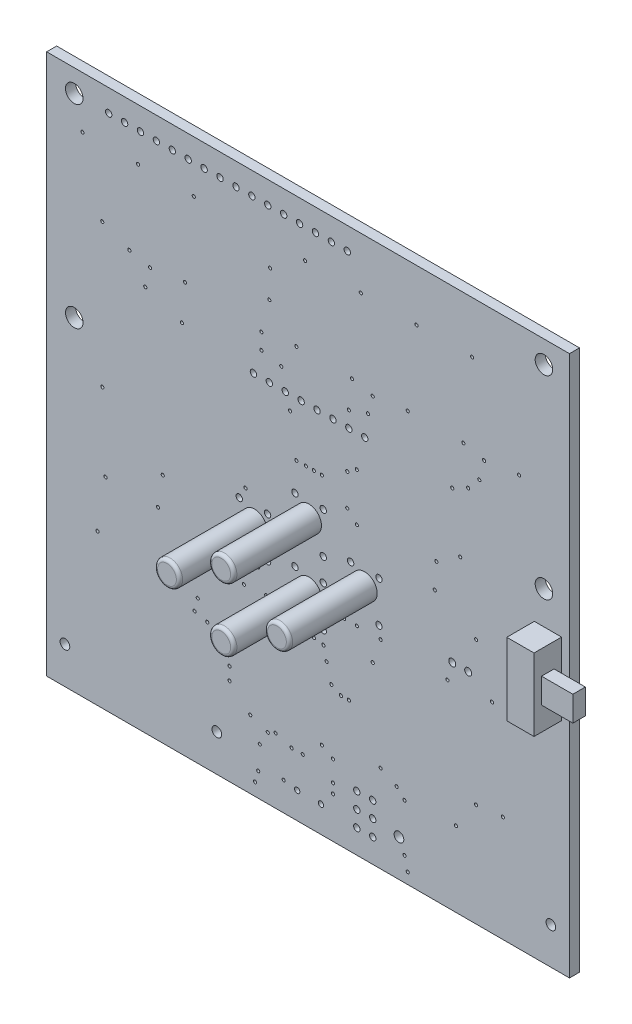
SolidWorks part; units mm, degrees
ref_plane "Front Plane" through (0, 0, 0) normal (0, 0, 1) x (1, 0, 0)
ref_plane "Top Plane" through (0, 0, 0) normal (0, 1, 0) x (1, 0, 0)
ref_plane "Right Plane" through (0, 0, 0) normal (1, 0, 0) x (0, 0, -1)
sketch "20" plane through (0, 0, 0) normal (0, 0, 1) x (1, 0, 0)
  line L0 (0, 86.36) -> (0, 0.02)
  line L1 (0, 0.02) -> (83.49, 0.02)
  line L2 (83.49, 0.02) -> (83.49, 86.36)
  line L3 (83.49, 86.36) -> (0, 86.36)
  circle A1 centre (40.01, 4.232) radius 0.425
  circle A2 centre (43.81, 4.232) radius 0.425
  circle A3 centre (27.18, 5.91) radius 0.775
  circle A4 centre (2.92, 5.91) radius 0.775
  circle A5 centre (80.52, 5.91) radius 0.775
  circle A6 centre (56.26, 5.91) radius 0.775
  circle A7 centre (4.41, 82.81) radius 1.4
  circle A8 centre (4.41, 51.81) radius 1.4
  circle A9 centre (79.41, 82.81) radius 1.4
  circle A10 centre (79.41, 51.81) radius 1.4
sketch "21" plane through (0, 0, 0) normal (0, 0, 1) x (1, 0, 0)
  line L120 (37.9171, 5.014) -> (37.9171, 4.032)
  line L121 (37.9171, 4.032) -> (37.91, 4.032)
  line L122 (37.91, 5.032) -> (38.91, 5.032)
  line L123 (45.91, 4.032) -> (45.91, 5.032)
  line L124 (45.91, 5.032) -> (44.91, 5.032)
  line L125 (37.91, 1.032) -> (37.91, 0.032)
  line L126 (45.91, 1.032) -> (45.91, 0.032)
  line L127 (47.625, 59.69) -> (48.895, 59.69)
  line L128 (48.895, 59.69) -> (49.53, 59.055)
  line L129 (49.53, 57.785) -> (48.895, 57.15)
  line L130 (44.45, 59.055) -> (45.085, 59.69)
  line L131 (45.085, 59.69) -> (46.355, 59.69)
  line L132 (46.355, 59.69) -> (46.99, 59.055)
  line L133 (46.99, 57.785) -> (46.355, 57.15)
  line L134 (46.355, 57.15) -> (45.085, 57.15)
  line L135 (45.085, 57.15) -> (44.45, 57.785)
  line L136 (47.625, 59.69) -> (46.99, 59.055)
  line L137 (46.99, 57.785) -> (47.625, 57.15)
  line L138 (48.895, 57.15) -> (47.625, 57.15)
  line L139 (40.005, 59.69) -> (41.275, 59.69)
  line L140 (41.275, 59.69) -> (41.91, 59.055)
  line L141 (41.91, 57.785) -> (41.275, 57.15)
  line L142 (41.91, 59.055) -> (42.545, 59.69)
  line L143 (42.545, 59.69) -> (43.815, 59.69)
  line L144 (43.815, 59.69) -> (44.45, 59.055)
  line L145 (44.45, 57.785) -> (43.815, 57.15)
  line L146 (43.815, 57.15) -> (42.545, 57.15)
  line L147 (42.545, 57.15) -> (41.91, 57.785)
  line L148 (36.83, 59.055) -> (37.465, 59.69)
  line L149 (37.465, 59.69) -> (38.735, 59.69)
  line L150 (38.735, 59.69) -> (39.37, 59.055)
  line L151 (39.37, 57.785) -> (38.735, 57.15)
  line L152 (38.735, 57.15) -> (37.465, 57.15)
  line L153 (37.465, 57.15) -> (36.83, 57.785)
  line L154 (40.005, 59.69) -> (39.37, 59.055)
  line L155 (39.37, 57.785) -> (40.005, 57.15)
  line L156 (41.275, 57.15) -> (40.005, 57.15)
  line L157 (32.385, 59.69) -> (33.655, 59.69)
  line L158 (33.655, 59.69) -> (34.29, 59.055)
  line L159 (34.29, 57.785) -> (33.655, 57.15)
  line L160 (34.29, 59.055) -> (34.925, 59.69)
  line L161 (34.925, 59.69) -> (36.195, 59.69)
  line L162 (36.195, 59.69) -> (36.83, 59.055)
  line L163 (36.83, 57.785) -> (36.195, 57.15)
  line L164 (36.195, 57.15) -> (34.925, 57.15)
  line L165 (34.925, 57.15) -> (34.29, 57.785)
  line L166 (31.75, 59.055) -> (31.75, 57.785)
  line L167 (32.385, 59.69) -> (31.75, 59.055)
  line L168 (31.75, 57.785) -> (32.385, 57.15)
  line L169 (33.655, 57.15) -> (32.385, 57.15)
  line L170 (50.165, 59.69) -> (51.435, 59.69)
  line L171 (51.435, 59.69) -> (52.07, 59.055)
  line L172 (52.07, 59.055) -> (52.07, 57.785)
  line L173 (52.07, 57.785) -> (51.435, 57.15)
  line L174 (50.165, 59.69) -> (49.53, 59.055)
  line L175 (49.53, 57.785) -> (50.165, 57.15)
  line L176 (51.435, 57.15) -> (50.165, 57.15)
  line L181 (44.958, 29.591) -> (44.958, 33.909)
  line L182 (38.862, 33.909) -> (38.862, 29.591)
  line L183 (42.908, 28.702) -> (40.894, 28.702)
  line L184 (42.938, 34.798) -> (40.894, 34.798)
  line L189 (44.958, 39.751) -> (44.958, 44.069)
  line L190 (38.862, 44.069) -> (38.862, 39.751)
  line L191 (42.908, 38.862) -> (40.894, 38.862)
  line L192 (42.938, 44.958) -> (40.894, 44.958)
  line L193 (53.848, 34.671) -> (53.848, 38.989)
  line L194 (47.752, 38.989) -> (47.752, 34.671)
  line L195 (51.798, 33.782) -> (49.784, 33.782)
  line L196 (51.828, 39.878) -> (49.784, 39.878)
  line L197 (36.068, 34.671) -> (36.068, 38.989)
  line L198 (29.972, 38.989) -> (29.972, 34.671)
  line L199 (34.018, 33.782) -> (32.004, 33.782)
  line L200 (34.048, 39.878) -> (32.004, 39.878)
  line L201 (82.185, 46.455) -> (77.835, 46.455)
  line L202 (77.835, 46.455) -> (77.835, 34.825)
  line L203 (77.835, 34.825) -> (82.185, 34.825)
  line L204 (82.185, 34.825) -> (82.185, 46.455)
  line L268 (25.259, 29.305) -> (29.658, 29.305)
  line L269 (29.658, 29.305) -> (29.658, 23.971)
  line L270 (29.558, 7.361) -> (29.558, 0.322)
  line L271 (29.558, 0.322) -> (28.14, 0.31)
  line L272 (0.913, 6.199) -> (0.913, 0.322)
  line L273 (0.913, 0.322) -> (1.891, 0.322)
  line L274 (1.002, 29.305) -> (0.913, 29.305)
  line L275 (0.913, 29.305) -> (0.913, 23.971)
  line L276 (78.599, 29.305) -> (82.998, 29.305)
  line L277 (82.998, 29.305) -> (82.998, 23.971)
  line L278 (82.898, 7.361) -> (82.898, 0.322)
  line L279 (82.898, 0.322) -> (81.48, 0.31)
  line L280 (54.253, 6.199) -> (54.253, 0.322)
  line L281 (54.253, 0.322) -> (55.231, 0.322)
  line L282 (54.342, 29.305) -> (54.253, 29.305)
  line L283 (54.253, 29.305) -> (54.253, 23.971)
  line L284 (1.91, 85.31) -> (81.91, 85.31)
  line L285 (81.91, 85.31) -> (81.91, 49.31)
  line L286 (81.91, 49.31) -> (1.91, 49.31)
  line L287 (1.91, 49.31) -> (1.91, 85.31)
  line L288 (6.26, 80.46) -> (77.56, 80.46)
  line L289 (77.56, 80.46) -> (77.56, 54.16)
  line L290 (77.56, 54.16) -> (6.26, 54.16)
  line L291 (6.26, 54.16) -> (6.26, 80.46)
  arc A255 (37.8409, 4.032) -> (37.9933, 4.032) centre (37.9171, 4.032) ccw
  arc A256 (37.9933, 5.014) -> (37.8409, 5.014) centre (37.9171, 5.014) ccw
  arc A257 (37.91, 4.1082) -> (37.91, 3.9558) centre (37.91, 4.032) ccw
  arc A258 (37.9171, 3.9558) -> (37.9171, 4.1082) centre (37.9171, 4.032) ccw
  arc A259 (38.91, 4.9558) -> (38.91, 5.1082) centre (38.91, 5.032) ccw
  arc A260 (37.91, 5.1082) -> (37.91, 4.9558) centre (37.91, 5.032) ccw
  arc A261 (45.9862, 5.032) -> (45.8338, 5.032) centre (45.91, 5.032) ccw
  arc A262 (45.8338, 4.032) -> (45.9862, 4.032) centre (45.91, 4.032) ccw
  arc A263 (44.91, 5.1082) -> (44.91, 4.9558) centre (44.91, 5.032) ccw
  arc A264 (45.91, 4.9558) -> (45.91, 5.1082) centre (45.91, 5.032) ccw
  arc A265 (37.8338, 0.032) -> (37.9862, 0.032) centre (37.91, 0.032) ccw
  arc A266 (37.9862, 1.032) -> (37.8338, 1.032) centre (37.91, 1.032) ccw
  arc A267 (45.8338, 0.032) -> (45.9862, 0.032) centre (45.91, 0.032) ccw
  arc A268 (45.9862, 1.032) -> (45.8338, 1.032) centre (45.91, 1.032) ccw
  arc A269 (48.895, 59.6392) -> (48.895, 59.7408) centre (48.895, 59.69) ccw
  arc A270 (47.625, 59.7408) -> (47.625, 59.6392) centre (47.625, 59.69) ccw
  arc A271 (49.4941, 59.0191) -> (49.5659, 59.0909) centre (49.53, 59.055) ccw
  arc A272 (48.9309, 59.7259) -> (48.8591, 59.6541) centre (48.895, 59.69) ccw
  arc A273 (48.8591, 57.1859) -> (48.9309, 57.1141) centre (48.895, 57.15) ccw
  arc A274 (49.5659, 57.7491) -> (49.4941, 57.8209) centre (49.53, 57.785) ccw
  arc A275 (45.1209, 59.6541) -> (45.0491, 59.7259) centre (45.085, 59.69) ccw
  arc A276 (44.4141, 59.0909) -> (44.4859, 59.0191) centre (44.45, 59.055) ccw
  arc A277 (46.355, 59.6392) -> (46.355, 59.7408) centre (46.355, 59.69) ccw
  arc A278 (45.085, 59.7408) -> (45.085, 59.6392) centre (45.085, 59.69) ccw
  arc A279 (46.9541, 59.0191) -> (47.0259, 59.0909) centre (46.99, 59.055) ccw
  arc A280 (46.3909, 59.7259) -> (46.3191, 59.6541) centre (46.355, 59.69) ccw
  arc A281 (46.3191, 57.1859) -> (46.3909, 57.1141) centre (46.355, 57.15) ccw
  arc A282 (47.0259, 57.7491) -> (46.9541, 57.8209) centre (46.99, 57.785) ccw
  arc A283 (45.085, 57.2008) -> (45.085, 57.0992) centre (45.085, 57.15) ccw
  arc A284 (46.355, 57.0992) -> (46.355, 57.2008) centre (46.355, 57.15) ccw
  arc A285 (44.4859, 57.8209) -> (44.4141, 57.7491) centre (44.45, 57.785) ccw
  arc A286 (45.0491, 57.1141) -> (45.1209, 57.1859) centre (45.085, 57.15) ccw
  arc A287 (46.9541, 59.0909) -> (47.0259, 59.0191) centre (46.99, 59.055) ccw
  arc A288 (47.6609, 59.6541) -> (47.5891, 59.7259) centre (47.625, 59.69) ccw
  arc A289 (47.5891, 57.1141) -> (47.6609, 57.1859) centre (47.625, 57.15) ccw
  arc A290 (47.0259, 57.8209) -> (46.9541, 57.7491) centre (46.99, 57.785) ccw
  arc A291 (47.625, 57.2008) -> (47.625, 57.0992) centre (47.625, 57.15) ccw
  arc A292 (48.895, 57.0992) -> (48.895, 57.2008) centre (48.895, 57.15) ccw
  arc A293 (41.275, 59.6392) -> (41.275, 59.7408) centre (41.275, 59.69) ccw
  arc A294 (40.005, 59.7408) -> (40.005, 59.6392) centre (40.005, 59.69) ccw
  arc A295 (41.8741, 59.0191) -> (41.9459, 59.0909) centre (41.91, 59.055) ccw
  arc A296 (41.3109, 59.7259) -> (41.2391, 59.6541) centre (41.275, 59.69) ccw
  arc A297 (41.2391, 57.1859) -> (41.3109, 57.1141) centre (41.275, 57.15) ccw
  arc A298 (41.9459, 57.7491) -> (41.8741, 57.8209) centre (41.91, 57.785) ccw
  arc A299 (42.5809, 59.6541) -> (42.5091, 59.7259) centre (42.545, 59.69) ccw
  arc A300 (41.8741, 59.0909) -> (41.9459, 59.0191) centre (41.91, 59.055) ccw
  arc A301 (43.815, 59.6392) -> (43.815, 59.7408) centre (43.815, 59.69) ccw
  arc A302 (42.545, 59.7408) -> (42.545, 59.6392) centre (42.545, 59.69) ccw
  arc A303 (44.4141, 59.0191) -> (44.4859, 59.0909) centre (44.45, 59.055) ccw
  arc A304 (43.8509, 59.7259) -> (43.7791, 59.6541) centre (43.815, 59.69) ccw
  arc A305 (43.7791, 57.1859) -> (43.8509, 57.1141) centre (43.815, 57.15) ccw
  arc A306 (44.4859, 57.7491) -> (44.4141, 57.8209) centre (44.45, 57.785) ccw
  arc A307 (42.545, 57.2008) -> (42.545, 57.0992) centre (42.545, 57.15) ccw
  arc A308 (43.815, 57.0992) -> (43.815, 57.2008) centre (43.815, 57.15) ccw
  arc A309 (41.9459, 57.8209) -> (41.8741, 57.7491) centre (41.91, 57.785) ccw
  arc A310 (42.5091, 57.1141) -> (42.5809, 57.1859) centre (42.545, 57.15) ccw
  arc A311 (37.5009, 59.6541) -> (37.4291, 59.7259) centre (37.465, 59.69) ccw
  arc A312 (36.7941, 59.0909) -> (36.8659, 59.0191) centre (36.83, 59.055) ccw
  arc A313 (38.735, 59.6392) -> (38.735, 59.7408) centre (38.735, 59.69) ccw
  arc A314 (37.465, 59.7408) -> (37.465, 59.6392) centre (37.465, 59.69) ccw
  arc A315 (39.3341, 59.0191) -> (39.4059, 59.0909) centre (39.37, 59.055) ccw
  arc A316 (38.7709, 59.7259) -> (38.6991, 59.6541) centre (38.735, 59.69) ccw
  arc A317 (38.6991, 57.1859) -> (38.7709, 57.1141) centre (38.735, 57.15) ccw
  arc A318 (39.4059, 57.7491) -> (39.3341, 57.8209) centre (39.37, 57.785) ccw
  arc A319 (37.465, 57.2008) -> (37.465, 57.0992) centre (37.465, 57.15) ccw
  arc A320 (38.735, 57.0992) -> (38.735, 57.2008) centre (38.735, 57.15) ccw
  arc A321 (36.8659, 57.8209) -> (36.7941, 57.7491) centre (36.83, 57.785) ccw
  arc A322 (37.4291, 57.1141) -> (37.5009, 57.1859) centre (37.465, 57.15) ccw
  arc A323 (39.3341, 59.0909) -> (39.4059, 59.0191) centre (39.37, 59.055) ccw
  arc A324 (40.0409, 59.6541) -> (39.9691, 59.7259) centre (40.005, 59.69) ccw
  arc A325 (39.9691, 57.1141) -> (40.0409, 57.1859) centre (40.005, 57.15) ccw
  arc A326 (39.4059, 57.8209) -> (39.3341, 57.7491) centre (39.37, 57.785) ccw
  arc A327 (40.005, 57.2008) -> (40.005, 57.0992) centre (40.005, 57.15) ccw
  arc A328 (41.275, 57.0992) -> (41.275, 57.2008) centre (41.275, 57.15) ccw
  arc A329 (33.655, 59.6392) -> (33.655, 59.7408) centre (33.655, 59.69) ccw
  arc A330 (32.385, 59.7408) -> (32.385, 59.6392) centre (32.385, 59.69) ccw
  arc A331 (34.2541, 59.0191) -> (34.3259, 59.0909) centre (34.29, 59.055) ccw
  arc A332 (33.6909, 59.7259) -> (33.6191, 59.6541) centre (33.655, 59.69) ccw
  arc A333 (33.6191, 57.1859) -> (33.6909, 57.1141) centre (33.655, 57.15) ccw
  arc A334 (34.3259, 57.7491) -> (34.2541, 57.8209) centre (34.29, 57.785) ccw
  arc A335 (34.9609, 59.6541) -> (34.8891, 59.7259) centre (34.925, 59.69) ccw
  arc A336 (34.2541, 59.0909) -> (34.3259, 59.0191) centre (34.29, 59.055) ccw
  arc A337 (36.195, 59.6392) -> (36.195, 59.7408) centre (36.195, 59.69) ccw
  arc A338 (34.925, 59.7408) -> (34.925, 59.6392) centre (34.925, 59.69) ccw
  arc A339 (36.7941, 59.0191) -> (36.8659, 59.0909) centre (36.83, 59.055) ccw
  arc A340 (36.2309, 59.7259) -> (36.1591, 59.6541) centre (36.195, 59.69) ccw
  arc A341 (36.1591, 57.1859) -> (36.2309, 57.1141) centre (36.195, 57.15) ccw
  arc A342 (36.8659, 57.7491) -> (36.7941, 57.8209) centre (36.83, 57.785) ccw
  arc A343 (34.925, 57.2008) -> (34.925, 57.0992) centre (34.925, 57.15) ccw
  arc A344 (36.195, 57.0992) -> (36.195, 57.2008) centre (36.195, 57.15) ccw
  arc A345 (34.3259, 57.8209) -> (34.2541, 57.7491) centre (34.29, 57.785) ccw
  arc A346 (34.8891, 57.1141) -> (34.9609, 57.1859) centre (34.925, 57.15) ccw
  arc A347 (31.6992, 57.785) -> (31.8008, 57.785) centre (31.75, 57.785) ccw
  arc A348 (31.8008, 59.055) -> (31.6992, 59.055) centre (31.75, 59.055) ccw
  arc A349 (31.7141, 59.0909) -> (31.7859, 59.0191) centre (31.75, 59.055) ccw
  arc A350 (32.4209, 59.6541) -> (32.3491, 59.7259) centre (32.385, 59.69) ccw
  arc A351 (32.3491, 57.1141) -> (32.4209, 57.1859) centre (32.385, 57.15) ccw
  arc A352 (31.7859, 57.8209) -> (31.7141, 57.7491) centre (31.75, 57.785) ccw
  arc A353 (32.385, 57.2008) -> (32.385, 57.0992) centre (32.385, 57.15) ccw
  arc A354 (33.655, 57.0992) -> (33.655, 57.2008) centre (33.655, 57.15) ccw
  arc A355 (51.435, 59.6392) -> (51.435, 59.7408) centre (51.435, 59.69) ccw
  arc A356 (50.165, 59.7408) -> (50.165, 59.6392) centre (50.165, 59.69) ccw
  arc A357 (52.0341, 59.0191) -> (52.1059, 59.0909) centre (52.07, 59.055) ccw
  arc A358 (51.4709, 59.7259) -> (51.3991, 59.6541) centre (51.435, 59.69) ccw
  arc A359 (52.0192, 57.785) -> (52.1208, 57.785) centre (52.07, 57.785) ccw
  arc A360 (52.1208, 59.055) -> (52.0192, 59.055) centre (52.07, 59.055) ccw
  arc A361 (51.3991, 57.1859) -> (51.4709, 57.1141) centre (51.435, 57.15) ccw
  arc A362 (52.1059, 57.7491) -> (52.0341, 57.8209) centre (52.07, 57.785) ccw
  arc A363 (49.4941, 59.0909) -> (49.5659, 59.0191) centre (49.53, 59.055) ccw
  arc A364 (50.2009, 59.6541) -> (50.1291, 59.7259) centre (50.165, 59.69) ccw
  arc A365 (50.1291, 57.1141) -> (50.2009, 57.1859) centre (50.165, 57.15) ccw
  arc A366 (49.5659, 57.8209) -> (49.4941, 57.7491) centre (49.53, 57.785) ccw
  arc A367 (50.165, 57.2008) -> (50.165, 57.0992) centre (50.165, 57.15) ccw
  arc A368 (51.435, 57.0992) -> (51.435, 57.2008) centre (51.435, 57.15) ccw
  arc A377 (45.0088, 33.909) -> (44.9072, 33.909) centre (44.958, 33.909) ccw
  arc A378 (44.9072, 29.591) -> (45.0088, 29.591) centre (44.958, 29.591) ccw
  arc A379 (38.8112, 29.591) -> (38.9128, 29.591) centre (38.862, 29.591) ccw
  arc A380 (38.9128, 33.909) -> (38.8112, 33.909) centre (38.862, 33.909) ccw
  arc A381 (40.894, 28.7528) -> (40.894, 28.6512) centre (40.894, 28.702) ccw
  arc A382 (42.908, 28.6512) -> (42.908, 28.7528) centre (42.908, 28.702) ccw
  arc A383 (40.894, 34.8488) -> (40.894, 34.7472) centre (40.894, 34.798) ccw
  arc A384 (42.938, 34.7472) -> (42.938, 34.8488) centre (42.938, 34.798) ccw
  circle A385 centre (41.91, 31.75) radius 1.778
  arc A395 (45.0088, 44.069) -> (44.9072, 44.069) centre (44.958, 44.069) ccw
  arc A396 (44.9072, 39.751) -> (45.0088, 39.751) centre (44.958, 39.751) ccw
  arc A397 (38.8112, 39.751) -> (38.9128, 39.751) centre (38.862, 39.751) ccw
  arc A398 (38.9128, 44.069) -> (38.8112, 44.069) centre (38.862, 44.069) ccw
  arc A399 (40.894, 38.9128) -> (40.894, 38.8112) centre (40.894, 38.862) ccw
  arc A400 (42.908, 38.8112) -> (42.908, 38.9128) centre (42.908, 38.862) ccw
  arc A401 (40.894, 45.0088) -> (40.894, 44.9072) centre (40.894, 44.958) ccw
  arc A402 (42.938, 44.9072) -> (42.938, 45.0088) centre (42.938, 44.958) ccw
  circle A403 centre (41.91, 41.91) radius 1.778
  arc A404 (53.8988, 38.989) -> (53.7972, 38.989) centre (53.848, 38.989) ccw
  arc A405 (53.7972, 34.671) -> (53.8988, 34.671) centre (53.848, 34.671) ccw
  arc A406 (47.7012, 34.671) -> (47.8028, 34.671) centre (47.752, 34.671) ccw
  arc A407 (47.8028, 38.989) -> (47.7012, 38.989) centre (47.752, 38.989) ccw
  arc A408 (49.784, 33.8328) -> (49.784, 33.7312) centre (49.784, 33.782) ccw
  arc A409 (51.798, 33.7312) -> (51.798, 33.8328) centre (51.798, 33.782) ccw
  arc A410 (49.784, 39.9288) -> (49.784, 39.8272) centre (49.784, 39.878) ccw
  arc A411 (51.828, 39.8272) -> (51.828, 39.9288) centre (51.828, 39.878) ccw
  circle A412 centre (50.8, 36.83) radius 1.778
  arc A413 (36.1188, 38.989) -> (36.0172, 38.989) centre (36.068, 38.989) ccw
  arc A414 (36.0172, 34.671) -> (36.1188, 34.671) centre (36.068, 34.671) ccw
  arc A415 (29.9212, 34.671) -> (30.0228, 34.671) centre (29.972, 34.671) ccw
  arc A416 (30.0228, 38.989) -> (29.9212, 38.989) centre (29.972, 38.989) ccw
  arc A417 (32.004, 33.8328) -> (32.004, 33.7312) centre (32.004, 33.782) ccw
  arc A418 (34.018, 33.7312) -> (34.018, 33.8328) centre (34.018, 33.782) ccw
  arc A419 (32.004, 39.9288) -> (32.004, 39.8272) centre (32.004, 39.878) ccw
  arc A420 (34.048, 39.8272) -> (34.048, 39.9288) centre (34.048, 39.878) ccw
  circle A421 centre (33.02, 36.83) radius 1.778
  arc A422 (77.835, 46.5058) -> (77.835, 46.4042) centre (77.835, 46.455) ccw
  arc A423 (82.185, 46.4042) -> (82.185, 46.5058) centre (82.185, 46.455) ccw
  arc A424 (77.7842, 34.825) -> (77.8858, 34.825) centre (77.835, 34.825) ccw
  arc A425 (77.8858, 46.455) -> (77.7842, 46.455) centre (77.835, 46.455) ccw
  arc A426 (82.185, 34.7742) -> (82.185, 34.8758) centre (82.185, 34.825) ccw
  arc A427 (77.835, 34.8758) -> (77.835, 34.7742) centre (77.835, 34.825) ccw
  arc A428 (82.2358, 46.455) -> (82.1342, 46.455) centre (82.185, 46.455) ccw
  arc A429 (82.1342, 34.825) -> (82.2358, 34.825) centre (82.185, 34.825) ccw
  arc A569 (29.658, 29.2415) -> (29.658, 29.3685) centre (29.658, 29.305) ccw
  arc A570 (25.259, 29.3685) -> (25.259, 29.2415) centre (25.259, 29.305) ccw
  arc A571 (29.5945, 23.971) -> (29.7215, 23.971) centre (29.658, 23.971) ccw
  arc A572 (29.7215, 29.305) -> (29.5945, 29.305) centre (29.658, 29.305) ccw
  arc A573 (29.4945, 0.322) -> (29.6215, 0.322) centre (29.558, 0.322) ccw
  arc A574 (29.6215, 7.361) -> (29.4945, 7.361) centre (29.558, 7.361) ccw
  arc A575 (28.1395, 0.3735) -> (28.1405, 0.2465) centre (28.14, 0.31) ccw
  arc A576 (29.5585, 0.2585) -> (29.5575, 0.3855) centre (29.558, 0.322) ccw
  arc A577 (0.8495, 0.322) -> (0.9765, 0.322) centre (0.913, 0.322) ccw
  arc A578 (0.9765, 6.199) -> (0.8495, 6.199) centre (0.913, 6.199) ccw
  arc A579 (1.891, 0.2585) -> (1.891, 0.3855) centre (1.891, 0.322) ccw
  arc A580 (0.913, 0.3855) -> (0.913, 0.2585) centre (0.913, 0.322) ccw
  arc A581 (0.913, 29.3685) -> (0.913, 29.2415) centre (0.913, 29.305) ccw
  arc A582 (1.002, 29.2415) -> (1.002, 29.3685) centre (1.002, 29.305) ccw
  arc A583 (0.8495, 23.971) -> (0.9765, 23.971) centre (0.913, 23.971) ccw
  arc A584 (0.9765, 29.305) -> (0.8495, 29.305) centre (0.913, 29.305) ccw
  arc A585 (82.998, 29.2415) -> (82.998, 29.3685) centre (82.998, 29.305) ccw
  arc A586 (78.599, 29.3685) -> (78.599, 29.2415) centre (78.599, 29.305) ccw
  arc A587 (82.9345, 23.971) -> (83.0615, 23.971) centre (82.998, 23.971) ccw
  arc A588 (83.0615, 29.305) -> (82.9345, 29.305) centre (82.998, 29.305) ccw
  arc A589 (82.8345, 0.322) -> (82.9615, 0.322) centre (82.898, 0.322) ccw
  arc A590 (82.9615, 7.361) -> (82.8345, 7.361) centre (82.898, 7.361) ccw
  arc A591 (81.4795, 0.3735) -> (81.4805, 0.2465) centre (81.48, 0.31) ccw
  arc A592 (82.8985, 0.2585) -> (82.8975, 0.3855) centre (82.898, 0.322) ccw
  arc A593 (54.1895, 0.322) -> (54.3165, 0.322) centre (54.253, 0.322) ccw
  arc A594 (54.3165, 6.199) -> (54.1895, 6.199) centre (54.253, 6.199) ccw
  arc A595 (55.231, 0.2585) -> (55.231, 0.3855) centre (55.231, 0.322) ccw
  arc A596 (54.253, 0.3855) -> (54.253, 0.2585) centre (54.253, 0.322) ccw
  arc A597 (54.253, 29.3685) -> (54.253, 29.2415) centre (54.253, 29.305) ccw
  arc A598 (54.342, 29.2415) -> (54.342, 29.3685) centre (54.342, 29.305) ccw
  arc A599 (54.1895, 23.971) -> (54.3165, 23.971) centre (54.253, 23.971) ccw
  arc A600 (54.3165, 29.305) -> (54.1895, 29.305) centre (54.253, 29.305) ccw
  arc A601 (81.91, 85.2592) -> (81.91, 85.3608) centre (81.91, 85.31) ccw
  arc A602 (1.91, 85.3608) -> (1.91, 85.2592) centre (1.91, 85.31) ccw
  arc A603 (81.8592, 49.31) -> (81.9608, 49.31) centre (81.91, 49.31) ccw
  arc A604 (81.9608, 85.31) -> (81.8592, 85.31) centre (81.91, 85.31) ccw
  arc A605 (1.91, 49.3608) -> (1.91, 49.2592) centre (1.91, 49.31) ccw
  arc A606 (81.91, 49.2592) -> (81.91, 49.3608) centre (81.91, 49.31) ccw
  arc A607 (1.9608, 85.31) -> (1.8592, 85.31) centre (1.91, 85.31) ccw
  arc A608 (1.8592, 49.31) -> (1.9608, 49.31) centre (1.91, 49.31) ccw
  arc A609 (77.56, 80.4092) -> (77.56, 80.5108) centre (77.56, 80.46) ccw
  arc A610 (6.26, 80.5108) -> (6.26, 80.4092) centre (6.26, 80.46) ccw
  arc A611 (77.5092, 54.16) -> (77.6108, 54.16) centre (77.56, 54.16) ccw
  arc A612 (77.6108, 80.46) -> (77.5092, 80.46) centre (77.56, 80.46) ccw
  arc A613 (6.26, 54.2108) -> (6.26, 54.1092) centre (6.26, 54.16) ccw
  arc A614 (77.56, 54.1092) -> (77.56, 54.2108) centre (77.56, 54.16) ccw
  arc A615 (6.3108, 80.46) -> (6.2092, 80.46) centre (6.26, 80.46) ccw
  arc A616 (6.2092, 54.16) -> (6.3108, 54.16) centre (6.26, 54.16) ccw
sketch "51" plane through (0, 0, 0) normal (0, 0, 1) x (1, 0, 0)
  line L199 (42.926, 28.702) -> (44.45, 28.702)
  line L200 (44.45, 28.702) -> (44.958, 29.21)
  line L201 (38.862, 29.21) -> (39.37, 28.702)
  line L202 (39.37, 28.702) -> (40.894, 28.702)
  line L203 (44.958, 34.29) -> (44.45, 34.798)
  line L204 (44.45, 34.798) -> (42.926, 34.798)
  line L205 (38.862, 34.29) -> (39.37, 34.798)
  line L206 (39.37, 34.798) -> (40.894, 34.798)
  line L207 (38.862, 29.21) -> (38.862, 29.591)
  line L208 (38.862, 34.29) -> (38.862, 33.909)
  line L209 (44.958, 34.29) -> (44.958, 33.909)
  line L210 (44.958, 29.21) -> (44.958, 29.591)
  line L211 (43.18, 34.29) -> (42.418, 34.29)
  line L212 (41.402, 34.29) -> (40.64, 34.29)
  line L213 (42.418, 34.29) -> (41.529, 33.909)
  line L221 (42.926, 38.862) -> (44.45, 38.862)
  line L222 (44.45, 38.862) -> (44.958, 39.37)
  line L223 (38.862, 39.37) -> (39.37, 38.862)
  line L224 (39.37, 38.862) -> (40.894, 38.862)
  line L225 (44.958, 44.45) -> (44.45, 44.958)
  line L226 (44.45, 44.958) -> (42.926, 44.958)
  line L227 (38.862, 44.45) -> (39.37, 44.958)
  line L228 (39.37, 44.958) -> (40.894, 44.958)
  line L229 (38.862, 39.37) -> (38.862, 39.751)
  line L230 (38.862, 44.45) -> (38.862, 44.069)
  line L231 (44.958, 44.45) -> (44.958, 44.069)
  line L232 (44.958, 39.37) -> (44.958, 39.751)
  line L233 (43.18, 44.45) -> (42.418, 44.45)
  line L234 (41.402, 44.45) -> (40.64, 44.45)
  line L235 (42.418, 44.45) -> (41.529, 44.069)
  line L236 (51.816, 33.782) -> (53.34, 33.782)
  line L237 (53.34, 33.782) -> (53.848, 34.29)
  line L238 (47.752, 34.29) -> (48.26, 33.782)
  line L239 (48.26, 33.782) -> (49.784, 33.782)
  line L240 (53.848, 39.37) -> (53.34, 39.878)
  line L241 (53.34, 39.878) -> (51.816, 39.878)
  line L242 (47.752, 39.37) -> (48.26, 39.878)
  line L243 (48.26, 39.878) -> (49.784, 39.878)
  line L244 (47.752, 34.29) -> (47.752, 34.671)
  line L245 (47.752, 39.37) -> (47.752, 38.989)
  line L246 (53.848, 39.37) -> (53.848, 38.989)
  line L247 (53.848, 34.29) -> (53.848, 34.671)
  line L248 (52.07, 39.37) -> (51.308, 39.37)
  line L249 (50.292, 39.37) -> (49.53, 39.37)
  line L250 (51.308, 39.37) -> (50.419, 38.989)
  line L251 (34.036, 33.782) -> (35.56, 33.782)
  line L252 (35.56, 33.782) -> (36.068, 34.29)
  line L253 (29.972, 34.29) -> (30.48, 33.782)
  line L254 (30.48, 33.782) -> (32.004, 33.782)
  line L255 (36.068, 39.37) -> (35.56, 39.878)
  line L256 (35.56, 39.878) -> (34.036, 39.878)
  line L257 (29.972, 39.37) -> (30.48, 39.878)
  line L258 (30.48, 39.878) -> (32.004, 39.878)
  line L259 (29.972, 34.29) -> (29.972, 34.671)
  line L260 (29.972, 39.37) -> (29.972, 38.989)
  line L261 (36.068, 39.37) -> (36.068, 38.989)
  line L262 (36.068, 34.29) -> (36.068, 34.671)
  line L263 (34.29, 39.37) -> (33.528, 39.37)
  line L264 (32.512, 39.37) -> (31.75, 39.37)
  line L265 (33.528, 39.37) -> (32.639, 38.989)
  line L270 (29.49, 29.21) -> (29.49, 0.41)
  line L271 (29.49, 0.41) -> (25.24, 0.41)
  line L272 (25.24, 0.41) -> (4.74, 0.41)
  line L273 (4.74, 0.41) -> (0.99, 0.41)
  line L274 (0.99, 0.41) -> (0.99, 29.21)
  line L275 (0.99, 29.21) -> (29.49, 29.21)
  line L276 (27.24, -6.39) -> (2.24, -6.39)
  line L277 (25.24, 0.41) -> (25.24, 1.21)
  line L278 (15.24, 11.21) -> (14.74, 11.21)
  line L279 (4.74, 1.21) -> (4.74, 0.41)
  line L280 (6.7704, -4.8596) -> (6.1857, -4.8596)
  line L281 (6.1857, -4.8596) -> (5.9908, -5.0545)
  line L282 (5.9908, -5.0545) -> (5.9908, -5.4443)
  line L283 (5.9908, -5.4443) -> (6.1857, -5.6392)
  line L284 (6.1857, -5.6392) -> (6.7704, -5.6392)
  line L285 (7.3551, -4.8596) -> (7.7449, -4.8596)
  line L286 (7.7449, -4.8596) -> (7.9398, -5.0545)
  line L287 (7.9398, -5.0545) -> (7.9398, -5.6392)
  line L288 (7.9398, -5.6392) -> (7.3551, -5.6392)
  line L289 (7.3551, -5.6392) -> (7.1602, -5.4443)
  line L290 (7.1602, -5.4443) -> (7.3551, -5.2494)
  line L291 (7.3551, -5.2494) -> (7.9398, -5.2494)
  line L292 (8.3296, -5.6392) -> (8.3296, -4.8596)
  line L293 (8.3296, -5.2494) -> (8.7194, -4.8596)
  line L294 (8.7194, -4.8596) -> (8.9143, -4.8596)
  line L295 (10.0837, -4.4698) -> (10.0837, -5.6392)
  line L296 (10.0837, -5.6392) -> (9.499, -5.6392)
  line L297 (9.499, -5.6392) -> (9.3041, -5.4443)
  line L298 (9.3041, -5.4443) -> (9.3041, -5.0545)
  line L299 (9.3041, -5.0545) -> (9.499, -4.8596)
  line L300 (9.499, -4.8596) -> (10.0837, -4.8596)
  line L301 (11.6429, -4.4698) -> (11.8378, -4.4698)
  line L302 (11.8378, -4.4698) -> (11.8378, -5.6392)
  line L303 (11.6429, -5.6392) -> (12.0327, -5.6392)
  line L304 (12.6174, -5.6392) -> (13.0072, -5.6392)
  line L305 (13.0072, -5.6392) -> (13.2021, -5.4443)
  line L306 (13.2021, -5.4443) -> (13.2021, -5.0545)
  line L307 (13.2021, -5.0545) -> (13.0072, -4.8596)
  line L308 (13.0072, -4.8596) -> (12.6174, -4.8596)
  line L309 (12.6174, -4.8596) -> (12.4225, -5.0545)
  line L310 (12.4225, -5.0545) -> (12.4225, -5.4443)
  line L311 (12.4225, -5.4443) -> (12.6174, -5.6392)
  line L312 (14.3715, -4.8596) -> (13.7868, -4.8596)
  line L313 (13.7868, -4.8596) -> (13.5919, -5.0545)
  line L314 (13.5919, -5.0545) -> (13.5919, -5.4443)
  line L315 (13.5919, -5.4443) -> (13.7868, -5.6392)
  line L316 (13.7868, -5.6392) -> (14.3715, -5.6392)
  line L317 (14.7613, -5.6392) -> (14.7613, -4.4698)
  line L318 (15.346, -5.6392) -> (14.7613, -5.2494)
  line L319 (14.7613, -5.2494) -> (15.346, -4.8596)
  line L320 (16.9052, -6.029) -> (16.9052, -4.8596)
  line L321 (16.9052, -4.8596) -> (17.4899, -4.8596)
  line L322 (17.4899, -4.8596) -> (17.6848, -5.0545)
  line L323 (17.6848, -5.0545) -> (17.6848, -5.4443)
  line L324 (17.6848, -5.4443) -> (17.4899, -5.6392)
  line L325 (17.4899, -5.6392) -> (16.9052, -5.6392)
  line L326 (18.2695, -5.6392) -> (18.6593, -5.6392)
  line L327 (18.6593, -5.6392) -> (18.8542, -5.4443)
  line L328 (18.8542, -5.4443) -> (18.8542, -5.0545)
  line L329 (18.8542, -5.0545) -> (18.6593, -4.8596)
  line L330 (18.6593, -4.8596) -> (18.2695, -4.8596)
  line L331 (18.2695, -4.8596) -> (18.0746, -5.0545)
  line L332 (18.0746, -5.0545) -> (18.0746, -5.4443)
  line L333 (18.0746, -5.4443) -> (18.2695, -5.6392)
  line L334 (19.244, -5.6392) -> (19.8287, -5.6392)
  line L335 (19.8287, -5.6392) -> (20.0236, -5.4443)
  line L336 (20.0236, -5.4443) -> (19.8287, -5.2494)
  line L337 (19.8287, -5.2494) -> (19.4389, -5.2494)
  line L338 (19.4389, -5.2494) -> (19.244, -5.0545)
  line L339 (19.244, -5.0545) -> (19.4389, -4.8596)
  line L340 (19.4389, -4.8596) -> (20.0236, -4.8596)
  line L341 (20.4134, -4.8596) -> (20.6083, -4.8596)
  line L342 (20.6083, -4.8596) -> (20.6083, -5.6392)
  line L343 (20.4134, -5.6392) -> (20.8032, -5.6392)
  line L344 (20.6083, -4.2749) -> (20.6083, -4.4698)
  line L345 (21.3879, -4.6647) -> (21.3879, -5.4443)
  line L346 (21.3879, -5.4443) -> (21.5828, -5.6392)
  line L347 (21.193, -4.8596) -> (21.5828, -4.8596)
  line L348 (21.9726, -4.8596) -> (22.1675, -4.8596)
  line L349 (22.1675, -4.8596) -> (22.1675, -5.6392)
  line L350 (21.9726, -5.6392) -> (22.3624, -5.6392)
  line L351 (22.1675, -4.2749) -> (22.1675, -4.4698)
  line L352 (22.947, -5.6392) -> (23.3368, -5.6392)
  line L353 (23.3368, -5.6392) -> (23.5317, -5.4443)
  line L354 (23.5317, -5.4443) -> (23.5317, -5.0545)
  line L355 (23.5317, -5.0545) -> (23.3368, -4.8596)
  line L356 (23.3368, -4.8596) -> (22.947, -4.8596)
  line L357 (22.947, -4.8596) -> (22.7522, -5.0545)
  line L358 (22.7522, -5.0545) -> (22.7522, -5.4443)
  line L359 (22.7522, -5.4443) -> (22.947, -5.6392)
  line L360 (23.9215, -5.6392) -> (23.9215, -4.8596)
  line L361 (23.9215, -4.8596) -> (24.5062, -4.8596)
  line L362 (24.5062, -4.8596) -> (24.7011, -5.0545)
  line L363 (24.7011, -5.0545) -> (24.7011, -5.6392)
  line L364 (82.83, 29.21) -> (82.83, 0.41)
  line L365 (82.83, 0.41) -> (78.58, 0.41)
  line L366 (78.58, 0.41) -> (58.08, 0.41)
  line L367 (58.08, 0.41) -> (54.33, 0.41)
  line L368 (54.33, 0.41) -> (54.33, 29.21)
  line L369 (54.33, 29.21) -> (82.83, 29.21)
  line L370 (80.58, -6.39) -> (55.58, -6.39)
  line L371 (78.58, 0.41) -> (78.58, 1.21)
  line L372 (68.58, 11.21) -> (68.08, 11.21)
  line L373 (58.08, 1.21) -> (58.08, 0.41)
  line L374 (60.1104, -4.8596) -> (59.5257, -4.8596)
  line L375 (59.5257, -4.8596) -> (59.3308, -5.0545)
  line L376 (59.3308, -5.0545) -> (59.3308, -5.4443)
  line L377 (59.3308, -5.4443) -> (59.5257, -5.6392)
  line L378 (59.5257, -5.6392) -> (60.1104, -5.6392)
  line L379 (60.6951, -4.8596) -> (61.0849, -4.8596)
  line L380 (61.0849, -4.8596) -> (61.2798, -5.0545)
  line L381 (61.2798, -5.0545) -> (61.2798, -5.6392)
  line L382 (61.2798, -5.6392) -> (60.6951, -5.6392)
  line L383 (60.6951, -5.6392) -> (60.5002, -5.4443)
  line L384 (60.5002, -5.4443) -> (60.6951, -5.2494)
  line L385 (60.6951, -5.2494) -> (61.2798, -5.2494)
  line L386 (61.6696, -5.6392) -> (61.6696, -4.8596)
  line L387 (61.6696, -5.2494) -> (62.0594, -4.8596)
  line L388 (62.0594, -4.8596) -> (62.2543, -4.8596)
  line L389 (63.4237, -4.4698) -> (63.4237, -5.6392)
  line L390 (63.4237, -5.6392) -> (62.839, -5.6392)
  line L391 (62.839, -5.6392) -> (62.6441, -5.4443)
  line L392 (62.6441, -5.4443) -> (62.6441, -5.0545)
  line L393 (62.6441, -5.0545) -> (62.839, -4.8596)
  line L394 (62.839, -4.8596) -> (63.4237, -4.8596)
  line L395 (64.9829, -4.4698) -> (65.1778, -4.4698)
  line L396 (65.1778, -4.4698) -> (65.1778, -5.6392)
  line L397 (64.9829, -5.6392) -> (65.3727, -5.6392)
  line L398 (65.9574, -5.6392) -> (66.3472, -5.6392)
  line L399 (66.3472, -5.6392) -> (66.5421, -5.4443)
  line L400 (66.5421, -5.4443) -> (66.5421, -5.0545)
  line L401 (66.5421, -5.0545) -> (66.3472, -4.8596)
  line L402 (66.3472, -4.8596) -> (65.9574, -4.8596)
  line L403 (65.9574, -4.8596) -> (65.7625, -5.0545)
  line L404 (65.7625, -5.0545) -> (65.7625, -5.4443)
  line L405 (65.7625, -5.4443) -> (65.9574, -5.6392)
  line L406 (67.7115, -4.8596) -> (67.1268, -4.8596)
  line L407 (67.1268, -4.8596) -> (66.9319, -5.0545)
  line L408 (66.9319, -5.0545) -> (66.9319, -5.4443)
  line L409 (66.9319, -5.4443) -> (67.1268, -5.6392)
  line L410 (67.1268, -5.6392) -> (67.7115, -5.6392)
  line L411 (68.1013, -5.6392) -> (68.1013, -4.4698)
  line L412 (68.686, -5.6392) -> (68.1013, -5.2494)
  line L413 (68.1013, -5.2494) -> (68.686, -4.8596)
  line L414 (70.2452, -6.029) -> (70.2452, -4.8596)
  line L415 (70.2452, -4.8596) -> (70.8299, -4.8596)
  line L416 (70.8299, -4.8596) -> (71.0248, -5.0545)
  line L417 (71.0248, -5.0545) -> (71.0248, -5.4443)
  line L418 (71.0248, -5.4443) -> (70.8299, -5.6392)
  line L419 (70.8299, -5.6392) -> (70.2452, -5.6392)
  line L420 (71.6095, -5.6392) -> (71.9993, -5.6392)
  line L421 (71.9993, -5.6392) -> (72.1942, -5.4443)
  line L422 (72.1942, -5.4443) -> (72.1942, -5.0545)
  line L423 (72.1942, -5.0545) -> (71.9993, -4.8596)
  line L424 (71.9993, -4.8596) -> (71.6095, -4.8596)
  line L425 (71.6095, -4.8596) -> (71.4146, -5.0545)
  line L426 (71.4146, -5.0545) -> (71.4146, -5.4443)
  line L427 (71.4146, -5.4443) -> (71.6095, -5.6392)
  line L428 (72.584, -5.6392) -> (73.1687, -5.6392)
  line L429 (73.1687, -5.6392) -> (73.3636, -5.4443)
  line L430 (73.3636, -5.4443) -> (73.1687, -5.2494)
  line L431 (73.1687, -5.2494) -> (72.7789, -5.2494)
  line L432 (72.7789, -5.2494) -> (72.584, -5.0545)
  line L433 (72.584, -5.0545) -> (72.7789, -4.8596)
  line L434 (72.7789, -4.8596) -> (73.3636, -4.8596)
  line L435 (73.7534, -4.8596) -> (73.9483, -4.8596)
  line L436 (73.9483, -4.8596) -> (73.9483, -5.6392)
  line L437 (73.7534, -5.6392) -> (74.1432, -5.6392)
  line L438 (73.9483, -4.2749) -> (73.9483, -4.4698)
  line L439 (74.7279, -4.6647) -> (74.7279, -5.4443)
  line L440 (74.7279, -5.4443) -> (74.9228, -5.6392)
  line L441 (74.533, -4.8596) -> (74.9228, -4.8596)
  line L442 (75.3126, -4.8596) -> (75.5075, -4.8596)
  line L443 (75.5075, -4.8596) -> (75.5075, -5.6392)
  line L444 (75.3126, -5.6392) -> (75.7024, -5.6392)
  line L445 (75.5075, -4.2749) -> (75.5075, -4.4698)
  line L446 (76.287, -5.6392) -> (76.6768, -5.6392)
  line L447 (76.6768, -5.6392) -> (76.8717, -5.4443)
  line L448 (76.8717, -5.4443) -> (76.8717, -5.0545)
  line L449 (76.8717, -5.0545) -> (76.6768, -4.8596)
  line L450 (76.6768, -4.8596) -> (76.287, -4.8596)
  line L451 (76.287, -4.8596) -> (76.0922, -5.0545)
  line L452 (76.0922, -5.0545) -> (76.0922, -5.4443)
  line L453 (76.0922, -5.4443) -> (76.287, -5.6392)
  line L454 (77.2615, -5.6392) -> (77.2615, -4.8596)
  line L455 (77.2615, -4.8596) -> (77.8462, -4.8596)
  line L456 (77.8462, -4.8596) -> (78.0411, -5.0545)
  line L457 (78.0411, -5.0545) -> (78.0411, -5.6392)
  arc A398 (44.45, 28.6512) -> (44.45, 28.7528) centre (44.45, 28.702) ccw
  arc A399 (42.926, 28.7528) -> (42.926, 28.6512) centre (42.926, 28.702) ccw
  arc A400 (44.9939, 29.1741) -> (44.9221, 29.2459) centre (44.958, 29.21) ccw
  arc A401 (44.4141, 28.7379) -> (44.4859, 28.6661) centre (44.45, 28.702) ccw
  arc A402 (39.3341, 28.6661) -> (39.4059, 28.7379) centre (39.37, 28.702) ccw
  arc A403 (38.8979, 29.2459) -> (38.8261, 29.1741) centre (38.862, 29.21) ccw
  arc A404 (40.894, 28.6512) -> (40.894, 28.7528) centre (40.894, 28.702) ccw
  arc A405 (39.37, 28.7528) -> (39.37, 28.6512) centre (39.37, 28.702) ccw
  arc A406 (44.4859, 34.8339) -> (44.4141, 34.7621) centre (44.45, 34.798) ccw
  arc A407 (44.9221, 34.2541) -> (44.9939, 34.3259) centre (44.958, 34.29) ccw
  arc A408 (42.926, 34.8488) -> (42.926, 34.7472) centre (42.926, 34.798) ccw
  arc A409 (44.45, 34.7472) -> (44.45, 34.8488) centre (44.45, 34.798) ccw
  arc A410 (39.4059, 34.7621) -> (39.3341, 34.8339) centre (39.37, 34.798) ccw
  arc A411 (38.8261, 34.3259) -> (38.8979, 34.2541) centre (38.862, 34.29) ccw
  arc A412 (40.894, 34.7472) -> (40.894, 34.8488) centre (40.894, 34.798) ccw
  arc A413 (39.37, 34.8488) -> (39.37, 34.7472) centre (39.37, 34.798) ccw
  arc A414 (38.9128, 29.591) -> (38.8112, 29.591) centre (38.862, 29.591) ccw
  arc A415 (38.8112, 29.21) -> (38.9128, 29.21) centre (38.862, 29.21) ccw
  arc A416 (38.8112, 33.909) -> (38.9128, 33.909) centre (38.862, 33.909) ccw
  arc A417 (38.9128, 34.29) -> (38.8112, 34.29) centre (38.862, 34.29) ccw
  arc A418 (44.9072, 33.909) -> (45.0088, 33.909) centre (44.958, 33.909) ccw
  arc A419 (45.0088, 34.29) -> (44.9072, 34.29) centre (44.958, 34.29) ccw
  arc A420 (45.0088, 29.591) -> (44.9072, 29.591) centre (44.958, 29.591) ccw
  arc A421 (44.9072, 29.21) -> (45.0088, 29.21) centre (44.958, 29.21) ccw
  arc A422 (42.418, 34.3408) -> (42.418, 34.2392) centre (42.418, 34.29) ccw
  arc A423 (43.18, 34.2392) -> (43.18, 34.3408) centre (43.18, 34.29) ccw
  arc A424 (40.64, 34.3408) -> (40.64, 34.2392) centre (40.64, 34.29) ccw
  arc A425 (41.402, 34.2392) -> (41.402, 34.3408) centre (41.402, 34.29) ccw
  arc A426 (41.509, 33.9557) -> (41.549, 33.8623) centre (41.529, 33.909) ccw
  arc A427 (42.438, 34.2433) -> (42.398, 34.3367) centre (42.418, 34.29) ccw
  arc A442 (44.45, 38.8112) -> (44.45, 38.9128) centre (44.45, 38.862) ccw
  arc A443 (42.926, 38.9128) -> (42.926, 38.8112) centre (42.926, 38.862) ccw
  arc A444 (44.9939, 39.3341) -> (44.9221, 39.4059) centre (44.958, 39.37) ccw
  arc A445 (44.4141, 38.8979) -> (44.4859, 38.8261) centre (44.45, 38.862) ccw
  arc A446 (39.3341, 38.8261) -> (39.4059, 38.8979) centre (39.37, 38.862) ccw
  arc A447 (38.8979, 39.4059) -> (38.8261, 39.3341) centre (38.862, 39.37) ccw
  arc A448 (40.894, 38.8112) -> (40.894, 38.9128) centre (40.894, 38.862) ccw
  arc A449 (39.37, 38.9128) -> (39.37, 38.8112) centre (39.37, 38.862) ccw
  arc A450 (44.4859, 44.9939) -> (44.4141, 44.9221) centre (44.45, 44.958) ccw
  arc A451 (44.9221, 44.4141) -> (44.9939, 44.4859) centre (44.958, 44.45) ccw
  arc A452 (42.926, 45.0088) -> (42.926, 44.9072) centre (42.926, 44.958) ccw
  arc A453 (44.45, 44.9072) -> (44.45, 45.0088) centre (44.45, 44.958) ccw
  arc A454 (39.4059, 44.9221) -> (39.3341, 44.9939) centre (39.37, 44.958) ccw
  arc A455 (38.8261, 44.4859) -> (38.8979, 44.4141) centre (38.862, 44.45) ccw
  arc A456 (40.894, 44.9072) -> (40.894, 45.0088) centre (40.894, 44.958) ccw
  arc A457 (39.37, 45.0088) -> (39.37, 44.9072) centre (39.37, 44.958) ccw
  arc A458 (38.9128, 39.751) -> (38.8112, 39.751) centre (38.862, 39.751) ccw
  arc A459 (38.8112, 39.37) -> (38.9128, 39.37) centre (38.862, 39.37) ccw
  arc A460 (38.8112, 44.069) -> (38.9128, 44.069) centre (38.862, 44.069) ccw
  arc A461 (38.9128, 44.45) -> (38.8112, 44.45) centre (38.862, 44.45) ccw
  arc A462 (44.9072, 44.069) -> (45.0088, 44.069) centre (44.958, 44.069) ccw
  arc A463 (45.0088, 44.45) -> (44.9072, 44.45) centre (44.958, 44.45) ccw
  arc A464 (45.0088, 39.751) -> (44.9072, 39.751) centre (44.958, 39.751) ccw
  arc A465 (44.9072, 39.37) -> (45.0088, 39.37) centre (44.958, 39.37) ccw
  arc A466 (42.418, 44.5008) -> (42.418, 44.3992) centre (42.418, 44.45) ccw
  arc A467 (43.18, 44.3992) -> (43.18, 44.5008) centre (43.18, 44.45) ccw
  arc A468 (40.64, 44.5008) -> (40.64, 44.3992) centre (40.64, 44.45) ccw
  arc A469 (41.402, 44.3992) -> (41.402, 44.5008) centre (41.402, 44.45) ccw
  arc A470 (41.509, 44.1157) -> (41.549, 44.0223) centre (41.529, 44.069) ccw
  arc A471 (42.438, 44.4033) -> (42.398, 44.4967) centre (42.418, 44.45) ccw
  arc A472 (53.34, 33.7312) -> (53.34, 33.8328) centre (53.34, 33.782) ccw
  arc A473 (51.816, 33.8328) -> (51.816, 33.7312) centre (51.816, 33.782) ccw
  arc A474 (53.8839, 34.2541) -> (53.8121, 34.3259) centre (53.848, 34.29) ccw
  arc A475 (53.3041, 33.8179) -> (53.3759, 33.7461) centre (53.34, 33.782) ccw
  arc A476 (48.2241, 33.7461) -> (48.2959, 33.8179) centre (48.26, 33.782) ccw
  arc A477 (47.7879, 34.3259) -> (47.7161, 34.2541) centre (47.752, 34.29) ccw
  arc A478 (49.784, 33.7312) -> (49.784, 33.8328) centre (49.784, 33.782) ccw
  arc A479 (48.26, 33.8328) -> (48.26, 33.7312) centre (48.26, 33.782) ccw
  arc A480 (53.3759, 39.9139) -> (53.3041, 39.8421) centre (53.34, 39.878) ccw
  arc A481 (53.8121, 39.3341) -> (53.8839, 39.4059) centre (53.848, 39.37) ccw
  arc A482 (51.816, 39.9288) -> (51.816, 39.8272) centre (51.816, 39.878) ccw
  arc A483 (53.34, 39.8272) -> (53.34, 39.9288) centre (53.34, 39.878) ccw
  arc A484 (48.2959, 39.8421) -> (48.2241, 39.9139) centre (48.26, 39.878) ccw
  arc A485 (47.7161, 39.4059) -> (47.7879, 39.3341) centre (47.752, 39.37) ccw
  arc A486 (49.784, 39.8272) -> (49.784, 39.9288) centre (49.784, 39.878) ccw
  arc A487 (48.26, 39.9288) -> (48.26, 39.8272) centre (48.26, 39.878) ccw
  arc A488 (47.8028, 34.671) -> (47.7012, 34.671) centre (47.752, 34.671) ccw
  arc A489 (47.7012, 34.29) -> (47.8028, 34.29) centre (47.752, 34.29) ccw
  arc A490 (47.7012, 38.989) -> (47.8028, 38.989) centre (47.752, 38.989) ccw
  arc A491 (47.8028, 39.37) -> (47.7012, 39.37) centre (47.752, 39.37) ccw
  arc A492 (53.7972, 38.989) -> (53.8988, 38.989) centre (53.848, 38.989) ccw
  arc A493 (53.8988, 39.37) -> (53.7972, 39.37) centre (53.848, 39.37) ccw
  arc A494 (53.8988, 34.671) -> (53.7972, 34.671) centre (53.848, 34.671) ccw
  arc A495 (53.7972, 34.29) -> (53.8988, 34.29) centre (53.848, 34.29) ccw
  arc A496 (51.308, 39.4208) -> (51.308, 39.3192) centre (51.308, 39.37) ccw
  arc A497 (52.07, 39.3192) -> (52.07, 39.4208) centre (52.07, 39.37) ccw
  arc A498 (49.53, 39.4208) -> (49.53, 39.3192) centre (49.53, 39.37) ccw
  arc A499 (50.292, 39.3192) -> (50.292, 39.4208) centre (50.292, 39.37) ccw
  arc A500 (50.399, 39.0357) -> (50.439, 38.9423) centre (50.419, 38.989) ccw
  arc A501 (51.328, 39.3233) -> (51.288, 39.4167) centre (51.308, 39.37) ccw
  arc A502 (35.56, 33.7312) -> (35.56, 33.8328) centre (35.56, 33.782) ccw
  arc A503 (34.036, 33.8328) -> (34.036, 33.7312) centre (34.036, 33.782) ccw
  arc A504 (36.1039, 34.2541) -> (36.0321, 34.3259) centre (36.068, 34.29) ccw
  arc A505 (35.5241, 33.8179) -> (35.5959, 33.7461) centre (35.56, 33.782) ccw
  arc A506 (30.4441, 33.7461) -> (30.5159, 33.8179) centre (30.48, 33.782) ccw
  arc A507 (30.0079, 34.3259) -> (29.9361, 34.2541) centre (29.972, 34.29) ccw
  arc A508 (32.004, 33.7312) -> (32.004, 33.8328) centre (32.004, 33.782) ccw
  arc A509 (30.48, 33.8328) -> (30.48, 33.7312) centre (30.48, 33.782) ccw
  arc A510 (35.5959, 39.9139) -> (35.5241, 39.8421) centre (35.56, 39.878) ccw
  arc A511 (36.0321, 39.3341) -> (36.1039, 39.4059) centre (36.068, 39.37) ccw
  arc A512 (34.036, 39.9288) -> (34.036, 39.8272) centre (34.036, 39.878) ccw
  arc A513 (35.56, 39.8272) -> (35.56, 39.9288) centre (35.56, 39.878) ccw
  arc A514 (30.5159, 39.8421) -> (30.4441, 39.9139) centre (30.48, 39.878) ccw
  arc A515 (29.9361, 39.4059) -> (30.0079, 39.3341) centre (29.972, 39.37) ccw
  arc A516 (32.004, 39.8272) -> (32.004, 39.9288) centre (32.004, 39.878) ccw
  arc A517 (30.48, 39.9288) -> (30.48, 39.8272) centre (30.48, 39.878) ccw
  arc A518 (30.0228, 34.671) -> (29.9212, 34.671) centre (29.972, 34.671) ccw
  arc A519 (29.9212, 34.29) -> (30.0228, 34.29) centre (29.972, 34.29) ccw
  arc A520 (29.9212, 38.989) -> (30.0228, 38.989) centre (29.972, 38.989) ccw
  arc A521 (30.0228, 39.37) -> (29.9212, 39.37) centre (29.972, 39.37) ccw
  arc A522 (36.0172, 38.989) -> (36.1188, 38.989) centre (36.068, 38.989) ccw
  arc A523 (36.1188, 39.37) -> (36.0172, 39.37) centre (36.068, 39.37) ccw
  arc A524 (36.1188, 34.671) -> (36.0172, 34.671) centre (36.068, 34.671) ccw
  arc A525 (36.0172, 34.29) -> (36.1188, 34.29) centre (36.068, 34.29) ccw
  arc A526 (33.528, 39.4208) -> (33.528, 39.3192) centre (33.528, 39.37) ccw
  arc A527 (34.29, 39.3192) -> (34.29, 39.4208) centre (34.29, 39.37) ccw
  arc A528 (31.75, 39.4208) -> (31.75, 39.3192) centre (31.75, 39.37) ccw
  arc A529 (32.512, 39.3192) -> (32.512, 39.4208) centre (32.512, 39.37) ccw
  arc A530 (32.619, 39.0357) -> (32.659, 38.9423) centre (32.639, 38.989) ccw
  arc A531 (33.548, 39.3233) -> (33.508, 39.4167) centre (33.528, 39.37) ccw
  arc A540 (29.4583, 0.41) -> (29.5218, 0.41) centre (29.4901, 0.41) ccw
  arc A541 (29.5218, 29.21) -> (29.4583, 29.21) centre (29.4901, 29.21) ccw
  arc A542 (25.24, 0.4418) -> (25.24, 0.3783) centre (25.24, 0.4101) ccw
  arc A543 (29.49, 0.3783) -> (29.49, 0.4418) centre (29.49, 0.4101) ccw
  arc A544 (4.74, 0.4418) -> (4.74, 0.3783) centre (4.74, 0.4101) ccw
  arc A545 (25.24, 0.3783) -> (25.24, 0.4418) centre (25.24, 0.4101) ccw
  arc A546 (0.99, 0.4418) -> (0.99, 0.3783) centre (0.99, 0.4101) ccw
  arc A547 (4.74, 0.3783) -> (4.74, 0.4418) centre (4.74, 0.4101) ccw
  arc A548 (1.0218, 29.21) -> (0.9583, 29.21) centre (0.9901, 29.21) ccw
  arc A549 (0.9583, 0.41) -> (1.0218, 0.41) centre (0.9901, 0.41) ccw
  arc A550 (29.49, 29.1783) -> (29.49, 29.2417) centre (29.49, 29.21) ccw
  arc A551 (0.99, 29.2417) -> (0.99, 29.1783) centre (0.99, 29.21) ccw
  arc A552 (2.24, -6.3583) -> (2.24, -6.4218) centre (2.24, -6.39) ccw
  arc A553 (27.24, -6.4218) -> (27.24, -6.3583) centre (27.24, -6.39) ccw
  arc A554 (25.2718, 1.21) -> (25.2083, 1.21) centre (25.2401, 1.21) ccw
  arc A555 (25.2083, 0.41) -> (25.2718, 0.41) centre (25.2401, 0.41) ccw
  arc A556 (25.24, 1.21) -> (15.24, 11.21) centre (15.2398, 1.2098) ccw
  arc A557 (25.2083, 1.21) -> (25.2718, 1.21) centre (25.2401, 1.21) ccw
  arc A558 (15.24, 11.2418) -> (15.24, 11.1783) centre (15.24, 11.21) ccw
  arc A559 (14.74, 11.21) -> (4.74, 1.21) centre (14.7402, 1.2098) ccw
  arc A560 (14.74, 11.1783) -> (14.74, 11.2418) centre (14.74, 11.21) ccw
  arc A561 (4.7083, 1.21) -> (4.7717, 1.21) centre (4.74, 1.21) ccw
  arc A562 (14.74, 11.2418) -> (14.74, 11.1783) centre (14.74, 11.21) ccw
  arc A563 (15.24, 11.1783) -> (15.24, 11.2418) centre (15.24, 11.21) ccw
  arc A564 (4.7083, 0.41) -> (4.7717, 0.41) centre (4.74, 0.41) ccw
  arc A565 (4.7717, 1.21) -> (4.7083, 1.21) centre (4.74, 1.21) ccw
  arc A566 (6.1857, -4.8342) -> (6.1857, -4.885) centre (6.1857, -4.8596) ccw
  arc A567 (6.7704, -4.885) -> (6.7704, -4.8342) centre (6.7704, -4.8596) ccw
  arc A568 (5.9728, -5.0365) -> (6.0088, -5.0725) centre (5.9908, -5.0545) ccw
  arc A569 (6.2037, -4.8776) -> (6.1677, -4.8416) centre (6.1857, -4.8596) ccw
  arc A570 (5.9654, -5.4443) -> (6.0162, -5.4443) centre (5.9908, -5.4443) ccw
  arc A571 (6.0162, -5.0545) -> (5.9654, -5.0545) centre (5.9908, -5.0545) ccw
  arc A572 (6.1677, -5.6572) -> (6.2037, -5.6212) centre (6.1857, -5.6392) ccw
  arc A573 (6.0088, -5.4263) -> (5.9728, -5.4623) centre (5.9908, -5.4443) ccw
  arc A574 (6.7704, -5.6646) -> (6.7704, -5.6138) centre (6.7704, -5.6392) ccw
  arc A575 (6.1857, -5.6138) -> (6.1857, -5.6646) centre (6.1857, -5.6392) ccw
  arc A576 (7.7449, -4.885) -> (7.7449, -4.8342) centre (7.7449, -4.8596) ccw
  arc A577 (7.3551, -4.8342) -> (7.3551, -4.885) centre (7.3551, -4.8596) ccw
  arc A578 (7.9218, -5.0725) -> (7.9578, -5.0365) centre (7.9398, -5.0545) ccw
  arc A579 (7.7629, -4.8416) -> (7.7269, -4.8776) centre (7.7449, -4.8596) ccw
  arc A580 (7.9144, -5.6392) -> (7.9652, -5.6392) centre (7.9398, -5.6392) ccw
  arc A581 (7.9652, -5.0545) -> (7.9144, -5.0545) centre (7.9398, -5.0545) ccw
  arc A582 (7.3551, -5.6138) -> (7.3551, -5.6646) centre (7.3551, -5.6392) ccw
  arc A583 (7.9398, -5.6646) -> (7.9398, -5.6138) centre (7.9398, -5.6392) ccw
  arc A584 (7.1782, -5.4263) -> (7.1422, -5.4623) centre (7.1602, -5.4443) ccw
  arc A585 (7.3371, -5.6572) -> (7.3731, -5.6212) centre (7.3551, -5.6392) ccw
  arc A586 (7.3731, -5.2674) -> (7.3371, -5.2314) centre (7.3551, -5.2494) ccw
  arc A587 (7.1422, -5.4263) -> (7.1782, -5.4623) centre (7.1602, -5.4443) ccw
  arc A588 (7.9398, -5.2748) -> (7.9398, -5.224) centre (7.9398, -5.2494) ccw
  arc A589 (7.3551, -5.224) -> (7.3551, -5.2748) centre (7.3551, -5.2494) ccw
  arc A590 (8.355, -4.8596) -> (8.3042, -4.8596) centre (8.3296, -4.8596) ccw
  arc A591 (8.3042, -5.6392) -> (8.355, -5.6392) centre (8.3296, -5.6392) ccw
  arc A592 (8.7374, -4.8776) -> (8.7014, -4.8416) centre (8.7194, -4.8596) ccw
  arc A593 (8.3116, -5.2314) -> (8.3476, -5.2674) centre (8.3296, -5.2494) ccw
  arc A594 (8.9143, -4.885) -> (8.9143, -4.8342) centre (8.9143, -4.8596) ccw
  arc A595 (8.7194, -4.8342) -> (8.7194, -4.885) centre (8.7194, -4.8596) ccw
  arc A596 (10.0583, -5.6392) -> (10.1091, -5.6392) centre (10.0837, -5.6392) ccw
  arc A597 (10.1091, -4.4698) -> (10.0583, -4.4698) centre (10.0837, -4.4698) ccw
  arc A598 (9.499, -5.6138) -> (9.499, -5.6646) centre (9.499, -5.6392) ccw
  arc A599 (10.0837, -5.6646) -> (10.0837, -5.6138) centre (10.0837, -5.6392) ccw
  arc A600 (9.3221, -5.4263) -> (9.2861, -5.4623) centre (9.3041, -5.4443) ccw
  arc A601 (9.481, -5.6572) -> (9.5169, -5.6212) centre (9.4989, -5.6392) ccw
  arc A602 (9.3295, -5.0545) -> (9.2787, -5.0545) centre (9.3041, -5.0545) ccw
  arc A603 (9.2787, -5.4443) -> (9.3295, -5.4443) centre (9.3041, -5.4443) ccw
  arc A604 (9.5169, -4.8776) -> (9.481, -4.8416) centre (9.4989, -4.8596) ccw
  arc A605 (9.2861, -5.0365) -> (9.3221, -5.0725) centre (9.3041, -5.0545) ccw
  arc A606 (10.0837, -4.885) -> (10.0837, -4.8342) centre (10.0837, -4.8596) ccw
  arc A607 (9.499, -4.8342) -> (9.499, -4.885) centre (9.499, -4.8596) ccw
  arc A608 (11.8378, -4.4952) -> (11.8378, -4.4444) centre (11.8378, -4.4698) ccw
  arc A609 (11.6429, -4.4444) -> (11.6429, -4.4952) centre (11.6429, -4.4698) ccw
  arc A610 (11.8124, -5.6392) -> (11.8632, -5.6392) centre (11.8378, -5.6392) ccw
  arc A611 (11.8632, -4.4698) -> (11.8124, -4.4698) centre (11.8378, -4.4698) ccw
  arc A612 (12.0327, -5.6646) -> (12.0327, -5.6138) centre (12.0327, -5.6392) ccw
  arc A613 (11.6429, -5.6138) -> (11.6429, -5.6646) centre (11.6429, -5.6392) ccw
  arc A614 (13.0072, -5.6646) -> (13.0072, -5.6138) centre (13.0072, -5.6392) ccw
  arc A615 (12.6174, -5.6138) -> (12.6174, -5.6646) centre (12.6174, -5.6392) ccw
  arc A616 (13.22, -5.4623) -> (13.1841, -5.4263) centre (13.202, -5.4443) ccw
  arc A617 (12.9892, -5.6212) -> (13.0251, -5.6572) centre (13.0072, -5.6392) ccw
  arc A618 (13.2275, -5.0545) -> (13.1767, -5.0545) centre (13.2021, -5.0545) ccw
  arc A619 (13.1767, -5.4443) -> (13.2275, -5.4443) centre (13.2021, -5.4443) ccw
  arc A620 (13.0251, -4.8416) -> (12.9892, -4.8776) centre (13.0072, -4.8596) ccw
  arc A621 (13.1841, -5.0725) -> (13.22, -5.0365) centre (13.202, -5.0545) ccw
  arc A622 (12.6174, -4.8342) -> (12.6174, -4.885) centre (12.6174, -4.8596) ccw
  arc A623 (13.0072, -4.885) -> (13.0072, -4.8342) centre (13.0072, -4.8596) ccw
  arc A624 (12.4045, -5.0365) -> (12.4404, -5.0725) centre (12.4225, -5.0545) ccw
  arc A625 (12.6353, -4.8776) -> (12.5994, -4.8416) centre (12.6174, -4.8596) ccw
  arc A626 (12.3971, -5.4443) -> (12.4479, -5.4443) centre (12.4225, -5.4443) ccw
  arc A627 (12.4479, -5.0545) -> (12.3971, -5.0545) centre (12.4225, -5.0545) ccw
  arc A628 (12.5994, -5.6572) -> (12.6353, -5.6212) centre (12.6174, -5.6392) ccw
  arc A629 (12.4404, -5.4263) -> (12.4045, -5.4623) centre (12.4225, -5.4443) ccw
  arc A630 (13.7868, -4.8342) -> (13.7868, -4.885) centre (13.7868, -4.8596) ccw
  arc A631 (14.3715, -4.885) -> (14.3715, -4.8342) centre (14.3715, -4.8596) ccw
  arc A632 (13.5739, -5.0365) -> (13.6098, -5.0725) centre (13.5918, -5.0545) ccw
  arc A633 (13.8047, -4.8776) -> (13.7688, -4.8416) centre (13.7867, -4.8596) ccw
  arc A634 (13.5665, -5.4443) -> (13.6173, -5.4443) centre (13.5919, -5.4443) ccw
  arc A635 (13.6173, -5.0545) -> (13.5665, -5.0545) centre (13.5919, -5.0545) ccw
  arc A636 (13.7688, -5.6572) -> (13.8047, -5.6212) centre (13.7867, -5.6392) ccw
  arc A637 (13.6098, -5.4263) -> (13.5739, -5.4623) centre (13.5918, -5.4443) ccw
  arc A638 (14.3715, -5.6646) -> (14.3715, -5.6138) centre (14.3715, -5.6392) ccw
  arc A639 (13.7868, -5.6138) -> (13.7868, -5.6646) centre (13.7868, -5.6392) ccw
  arc A640 (14.7867, -4.4698) -> (14.7359, -4.4698) centre (14.7613, -4.4698) ccw
  arc A641 (14.7359, -5.6392) -> (14.7867, -5.6392) centre (14.7613, -5.6392) ccw
  arc A642 (14.7754, -5.2283) -> (14.7472, -5.2705) centre (14.7613, -5.2494) ccw
  arc A643 (15.3319, -5.6603) -> (15.3601, -5.6181) centre (15.346, -5.6392) ccw
  arc A644 (15.3601, -4.8807) -> (15.3319, -4.8385) centre (15.346, -4.8596) ccw
  arc A645 (14.7472, -5.2283) -> (14.7754, -5.2705) centre (14.7613, -5.2494) ccw
  arc A646 (16.9306, -4.8596) -> (16.8798, -4.8596) centre (16.9052, -4.8596) ccw
  arc A647 (16.8798, -6.029) -> (16.9306, -6.029) centre (16.9052, -6.029) ccw
  arc A648 (17.4899, -4.885) -> (17.4899, -4.8342) centre (17.4899, -4.8596) ccw
  arc A649 (16.9052, -4.8342) -> (16.9052, -4.885) centre (16.9052, -4.8596) ccw
  arc A650 (17.6668, -5.0725) -> (17.7027, -5.0365) centre (17.6847, -5.0545) ccw
  arc A651 (17.5078, -4.8416) -> (17.4719, -4.8776) centre (17.4899, -4.8596) ccw
  arc A652 (17.6594, -5.4443) -> (17.7102, -5.4443) centre (17.6848, -5.4443) ccw
  arc A653 (17.7102, -5.0545) -> (17.6594, -5.0545) centre (17.6848, -5.0545) ccw
  arc A654 (17.4719, -5.6212) -> (17.5078, -5.6572) centre (17.4899, -5.6392) ccw
  arc A655 (17.7027, -5.4623) -> (17.6668, -5.4263) centre (17.6847, -5.4443) ccw
  arc A656 (16.9052, -5.6138) -> (16.9052, -5.6646) centre (16.9052, -5.6392) ccw
  arc A657 (17.4899, -5.6646) -> (17.4899, -5.6138) centre (17.4899, -5.6392) ccw
  arc A658 (18.6593, -5.6646) -> (18.6593, -5.6138) centre (18.6593, -5.6392) ccw
  arc A659 (18.2695, -5.6138) -> (18.2695, -5.6646) centre (18.2695, -5.6392) ccw
  arc A660 (18.8721, -5.4623) -> (18.8362, -5.4263) centre (18.8542, -5.4443) ccw
  arc A661 (18.6413, -5.6212) -> (18.6772, -5.6572) centre (18.6593, -5.6392) ccw
  arc A662 (18.8796, -5.0545) -> (18.8288, -5.0545) centre (18.8542, -5.0545) ccw
  arc A663 (18.8288, -5.4443) -> (18.8796, -5.4443) centre (18.8542, -5.4443) ccw
  arc A664 (18.6772, -4.8416) -> (18.6413, -4.8776) centre (18.6593, -4.8596) ccw
  arc A665 (18.8362, -5.0725) -> (18.8721, -5.0365) centre (18.8542, -5.0545) ccw
  arc A666 (18.2695, -4.8342) -> (18.2695, -4.885) centre (18.2695, -4.8596) ccw
  arc A667 (18.6593, -4.885) -> (18.6593, -4.8342) centre (18.6593, -4.8596) ccw
  arc A668 (18.0566, -5.0365) -> (18.0925, -5.0725) centre (18.0746, -5.0545) ccw
  arc A669 (18.2874, -4.8776) -> (18.2515, -4.8416) centre (18.2694, -4.8596) ccw
  arc A670 (18.0492, -5.4443) -> (18.1, -5.4443) centre (18.0746, -5.4443) ccw
  arc A671 (18.1, -5.0545) -> (18.0492, -5.0545) centre (18.0746, -5.0545) ccw
  arc A672 (18.2515, -5.6572) -> (18.2874, -5.6212) centre (18.2694, -5.6392) ccw
  arc A673 (18.0925, -5.4263) -> (18.0566, -5.4623) centre (18.0746, -5.4443) ccw
  arc A674 (19.8287, -5.6646) -> (19.8287, -5.6138) centre (19.8287, -5.6392) ccw
  arc A675 (19.244, -5.6138) -> (19.244, -5.6646) centre (19.244, -5.6392) ccw
  arc A676 (20.0415, -5.4623) -> (20.0056, -5.4263) centre (20.0236, -5.4443) ccw
  arc A677 (19.8107, -5.6212) -> (19.8466, -5.6572) centre (19.8286, -5.6392) ccw
  arc A678 (19.8466, -5.2314) -> (19.8107, -5.2674) centre (19.8286, -5.2494) ccw
  arc A679 (20.0056, -5.4623) -> (20.0415, -5.4263) centre (20.0236, -5.4443) ccw
  arc A680 (19.4389, -5.224) -> (19.4389, -5.2748) centre (19.4389, -5.2494) ccw
  arc A681 (19.8287, -5.2748) -> (19.8287, -5.224) centre (19.8287, -5.2494) ccw
  arc A682 (19.2619, -5.0365) -> (19.226, -5.0725) centre (19.244, -5.0545) ccw
  arc A683 (19.4209, -5.2674) -> (19.4568, -5.2314) centre (19.4389, -5.2494) ccw
  arc A684 (19.4568, -4.8776) -> (19.4209, -4.8416) centre (19.4389, -4.8596) ccw
  arc A685 (19.226, -5.0365) -> (19.2619, -5.0725) centre (19.244, -5.0545) ccw
  arc A686 (20.0236, -4.885) -> (20.0236, -4.8342) centre (20.0236, -4.8596) ccw
  arc A687 (19.4389, -4.8342) -> (19.4389, -4.885) centre (19.4389, -4.8596) ccw
  arc A688 (20.6083, -4.885) -> (20.6083, -4.8342) centre (20.6083, -4.8596) ccw
  arc A689 (20.4134, -4.8342) -> (20.4134, -4.885) centre (20.4134, -4.8596) ccw
  arc A690 (20.5829, -5.6392) -> (20.6337, -5.6392) centre (20.6083, -5.6392) ccw
  arc A691 (20.6337, -4.8596) -> (20.5829, -4.8596) centre (20.6083, -4.8596) ccw
  arc A692 (20.8032, -5.6646) -> (20.8032, -5.6138) centre (20.8032, -5.6392) ccw
  arc A693 (20.4134, -5.6138) -> (20.4134, -5.6646) centre (20.4134, -5.6392) ccw
  arc A694 (20.5829, -4.4698) -> (20.6337, -4.4698) centre (20.6083, -4.4698) ccw
  arc A695 (20.6337, -4.2749) -> (20.5829, -4.2749) centre (20.6083, -4.2749) ccw
  arc A696 (21.3625, -5.4443) -> (21.4133, -5.4443) centre (21.3879, -5.4443) ccw
  arc A697 (21.4133, -4.6647) -> (21.3625, -4.6647) centre (21.3879, -4.6647) ccw
  arc A698 (21.5648, -5.6572) -> (21.6007, -5.6212) centre (21.5828, -5.6392) ccw
  arc A699 (21.4058, -5.4263) -> (21.3699, -5.4623) centre (21.3879, -5.4443) ccw
  arc A700 (21.5828, -4.885) -> (21.5828, -4.8342) centre (21.5828, -4.8596) ccw
  arc A701 (21.193, -4.8342) -> (21.193, -4.885) centre (21.193, -4.8596) ccw
  arc A702 (22.1675, -4.885) -> (22.1675, -4.8342) centre (22.1675, -4.8596) ccw
  arc A703 (21.9726, -4.8342) -> (21.9726, -4.885) centre (21.9726, -4.8596) ccw
  arc A704 (22.1421, -5.6392) -> (22.1929, -5.6392) centre (22.1675, -5.6392) ccw
  arc A705 (22.1929, -4.8596) -> (22.1421, -4.8596) centre (22.1675, -4.8596) ccw
  arc A706 (22.3624, -5.6646) -> (22.3624, -5.6138) centre (22.3624, -5.6392) ccw
  arc A707 (21.9726, -5.6138) -> (21.9726, -5.6646) centre (21.9726, -5.6392) ccw
  arc A708 (22.1421, -4.4698) -> (22.1929, -4.4698) centre (22.1675, -4.4698) ccw
  arc A709 (22.1929, -4.2749) -> (22.1421, -4.2749) centre (22.1675, -4.2749) ccw
  arc A710 (23.3368, -5.6646) -> (23.3368, -5.6138) centre (23.3368, -5.6392) ccw
  arc A711 (22.947, -5.6138) -> (22.947, -5.6646) centre (22.947, -5.6392) ccw
  arc A712 (23.5497, -5.4623) -> (23.5138, -5.4263) centre (23.5318, -5.4443) ccw
  arc A713 (23.3189, -5.6212) -> (23.3548, -5.6572) centre (23.3368, -5.6392) ccw
  arc A714 (23.5571, -5.0545) -> (23.5063, -5.0545) centre (23.5317, -5.0545) ccw
  arc A715 (23.5063, -5.4443) -> (23.5571, -5.4443) centre (23.5317, -5.4443) ccw
  arc A716 (23.3548, -4.8416) -> (23.3189, -4.8776) centre (23.3368, -4.8596) ccw
  arc A717 (23.5138, -5.0725) -> (23.5497, -5.0365) centre (23.5318, -5.0545) ccw
  arc A718 (22.947, -4.8342) -> (22.947, -4.885) centre (22.947, -4.8596) ccw
  arc A719 (23.3368, -4.885) -> (23.3368, -4.8342) centre (23.3368, -4.8596) ccw
  arc A720 (22.7342, -5.0365) -> (22.7701, -5.0725) centre (22.7522, -5.0545) ccw
  arc A721 (22.965, -4.8776) -> (22.9291, -4.8416) centre (22.947, -4.8596) ccw
  arc A722 (22.7267, -5.4443) -> (22.7776, -5.4443) centre (22.7522, -5.4443) ccw
  arc A723 (22.7776, -5.0545) -> (22.7267, -5.0545) centre (22.7522, -5.0545) ccw
  arc A724 (22.9291, -5.6572) -> (22.965, -5.6212) centre (22.947, -5.6392) ccw
  arc A725 (22.7701, -5.4263) -> (22.7342, -5.4623) centre (22.7522, -5.4443) ccw
  arc A726 (23.9469, -4.8596) -> (23.8961, -4.8596) centre (23.9215, -4.8596) ccw
  arc A727 (23.8961, -5.6392) -> (23.9469, -5.6392) centre (23.9215, -5.6392) ccw
  arc A728 (24.5062, -4.885) -> (24.5062, -4.8342) centre (24.5062, -4.8596) ccw
  arc A729 (23.9215, -4.8342) -> (23.9215, -4.885) centre (23.9215, -4.8596) ccw
  arc A730 (24.6832, -5.0725) -> (24.7191, -5.0365) centre (24.7011, -5.0545) ccw
  arc A731 (24.5242, -4.8416) -> (24.4883, -4.8776) centre (24.5063, -4.8596) ccw
  arc A732 (24.6757, -5.6392) -> (24.7265, -5.6392) centre (24.7011, -5.6392) ccw
  arc A733 (24.7265, -5.0545) -> (24.6757, -5.0545) centre (24.7011, -5.0545) ccw
  arc A734 (82.7982, 0.41) -> (82.8618, 0.41) centre (82.83, 0.41) ccw
  arc A735 (82.8618, 29.21) -> (82.7982, 29.21) centre (82.83, 29.21) ccw
  arc A736 (78.58, 0.4418) -> (78.58, 0.3783) centre (78.58, 0.4101) ccw
  arc A737 (82.83, 0.3783) -> (82.83, 0.4418) centre (82.83, 0.4101) ccw
  arc A738 (58.08, 0.4418) -> (58.08, 0.3783) centre (58.08, 0.4101) ccw
  arc A739 (78.58, 0.3783) -> (78.58, 0.4418) centre (78.58, 0.4101) ccw
  arc A740 (54.33, 0.4418) -> (54.33, 0.3783) centre (54.33, 0.4101) ccw
  arc A741 (58.08, 0.3783) -> (58.08, 0.4418) centre (58.08, 0.4101) ccw
  arc A743 (54.2983, 0.41) -> (54.3618, 0.41) centre (54.3301, 0.41) ccw
  arc A744 (82.83, 29.1783) -> (82.83, 29.2417) centre (82.83, 29.21) ccw
  arc A746 (55.58, -6.3583) -> (55.58, -6.4218) centre (55.58, -6.39) ccw
  arc A747 (80.58, -6.4218) -> (80.58, -6.3583) centre (80.58, -6.39) ccw
  arc A748 (78.6118, 1.21) -> (78.5482, 1.21) centre (78.58, 1.21) ccw
  arc A749 (78.5482, 0.41) -> (78.6118, 0.41) centre (78.58, 0.41) ccw
  arc A750 (78.58, 1.21) -> (68.58, 11.21) centre (68.5798, 1.2098) ccw
  arc A751 (78.5482, 1.21) -> (78.6118, 1.21) centre (78.58, 1.21) ccw
  arc A752 (68.58, 11.2418) -> (68.58, 11.1783) centre (68.58, 11.21) ccw
  arc A753 (68.08, 11.21) -> (58.08, 1.21) centre (68.0802, 1.2098) ccw
  arc A754 (68.08, 11.1783) -> (68.08, 11.2418) centre (68.08, 11.21) ccw
  arc A755 (58.0483, 1.21) -> (58.1118, 1.21) centre (58.08, 1.21) ccw
  arc A756 (68.08, 11.2418) -> (68.08, 11.1783) centre (68.08, 11.21) ccw
  arc A757 (68.58, 11.1783) -> (68.58, 11.2418) centre (68.58, 11.21) ccw
  arc A758 (58.0483, 0.41) -> (58.1118, 0.41) centre (58.08, 0.41) ccw
  arc A759 (58.1118, 1.21) -> (58.0483, 1.21) centre (58.08, 1.21) ccw
  arc A760 (59.5257, -4.8342) -> (59.5257, -4.885) centre (59.5257, -4.8596) ccw
  arc A761 (60.1104, -4.885) -> (60.1104, -4.8342) centre (60.1104, -4.8596) ccw
  arc A762 (59.3128, -5.0365) -> (59.3488, -5.0725) centre (59.3308, -5.0545) ccw
  arc A763 (59.5437, -4.8776) -> (59.5077, -4.8416) centre (59.5257, -4.8596) ccw
  arc A764 (59.3054, -5.4443) -> (59.3562, -5.4443) centre (59.3308, -5.4443) ccw
  arc A765 (59.3562, -5.0545) -> (59.3054, -5.0545) centre (59.3308, -5.0545) ccw
  arc A766 (59.5077, -5.6572) -> (59.5437, -5.6212) centre (59.5257, -5.6392) ccw
  arc A767 (59.3488, -5.4263) -> (59.3128, -5.4623) centre (59.3308, -5.4443) ccw
  arc A768 (60.1104, -5.6646) -> (60.1104, -5.6138) centre (60.1104, -5.6392) ccw
  arc A769 (59.5257, -5.6138) -> (59.5257, -5.6646) centre (59.5257, -5.6392) ccw
  arc A770 (61.0849, -4.885) -> (61.0849, -4.8342) centre (61.0849, -4.8596) ccw
  arc A771 (60.6951, -4.8342) -> (60.6951, -4.885) centre (60.6951, -4.8596) ccw
  arc A772 (61.2618, -5.0725) -> (61.2978, -5.0365) centre (61.2798, -5.0545) ccw
  arc A773 (61.1029, -4.8416) -> (61.0669, -4.8776) centre (61.0849, -4.8596) ccw
  arc A774 (61.2544, -5.6392) -> (61.3052, -5.6392) centre (61.2798, -5.6392) ccw
  arc A775 (61.3052, -5.0545) -> (61.2544, -5.0545) centre (61.2798, -5.0545) ccw
  arc A776 (60.6951, -5.6138) -> (60.6951, -5.6646) centre (60.6951, -5.6392) ccw
  arc A777 (61.2798, -5.6646) -> (61.2798, -5.6138) centre (61.2798, -5.6392) ccw
  arc A778 (60.5182, -5.4263) -> (60.4822, -5.4623) centre (60.5002, -5.4443) ccw
  arc A779 (60.6771, -5.6572) -> (60.7131, -5.6212) centre (60.6951, -5.6392) ccw
  arc A780 (60.7131, -5.2674) -> (60.6771, -5.2314) centre (60.6951, -5.2494) ccw
  arc A781 (60.4822, -5.4263) -> (60.5182, -5.4623) centre (60.5002, -5.4443) ccw
  arc A782 (61.2798, -5.2748) -> (61.2798, -5.224) centre (61.2798, -5.2494) ccw
  arc A783 (60.6951, -5.224) -> (60.6951, -5.2748) centre (60.6951, -5.2494) ccw
  arc A784 (61.695, -4.8596) -> (61.6442, -4.8596) centre (61.6696, -4.8596) ccw
  arc A785 (61.6442, -5.6392) -> (61.695, -5.6392) centre (61.6696, -5.6392) ccw
  arc A786 (62.0774, -4.8776) -> (62.0414, -4.8416) centre (62.0594, -4.8596) ccw
  arc A787 (61.6516, -5.2314) -> (61.6876, -5.2674) centre (61.6696, -5.2494) ccw
  arc A788 (62.2543, -4.885) -> (62.2543, -4.8342) centre (62.2543, -4.8596) ccw
  arc A789 (62.0594, -4.8342) -> (62.0594, -4.885) centre (62.0594, -4.8596) ccw
  arc A790 (63.3983, -5.6392) -> (63.4491, -5.6392) centre (63.4237, -5.6392) ccw
  arc A791 (63.4491, -4.4698) -> (63.3983, -4.4698) centre (63.4237, -4.4698) ccw
  arc A792 (62.839, -5.6138) -> (62.839, -5.6646) centre (62.839, -5.6392) ccw
  arc A793 (63.4237, -5.6646) -> (63.4237, -5.6138) centre (63.4237, -5.6392) ccw
  arc A794 (62.6621, -5.4263) -> (62.6261, -5.4623) centre (62.6441, -5.4443) ccw
  arc A795 (62.821, -5.6572) -> (62.8569, -5.6212) centre (62.839, -5.6392) ccw
  arc A796 (62.6695, -5.0545) -> (62.6187, -5.0545) centre (62.6441, -5.0545) ccw
  arc A797 (62.6187, -5.4443) -> (62.6695, -5.4443) centre (62.6441, -5.4443) ccw
  arc A798 (62.8569, -4.8776) -> (62.821, -4.8416) centre (62.839, -4.8596) ccw
  arc A799 (62.6261, -5.0365) -> (62.6621, -5.0725) centre (62.6441, -5.0545) ccw
  arc A800 (63.4237, -4.885) -> (63.4237, -4.8342) centre (63.4237, -4.8596) ccw
  arc A801 (62.839, -4.8342) -> (62.839, -4.885) centre (62.839, -4.8596) ccw
  arc A802 (65.1778, -4.4952) -> (65.1778, -4.4444) centre (65.1778, -4.4698) ccw
  arc A803 (64.9829, -4.4444) -> (64.9829, -4.4952) centre (64.9829, -4.4698) ccw
  arc A804 (65.1524, -5.6392) -> (65.2032, -5.6392) centre (65.1778, -5.6392) ccw
  arc A805 (65.2032, -4.4698) -> (65.1524, -4.4698) centre (65.1778, -4.4698) ccw
  arc A806 (65.3727, -5.6646) -> (65.3727, -5.6138) centre (65.3727, -5.6392) ccw
  arc A807 (64.9829, -5.6138) -> (64.9829, -5.6646) centre (64.9829, -5.6392) ccw
  arc A808 (66.3472, -5.6646) -> (66.3472, -5.6138) centre (66.3472, -5.6392) ccw
  arc A809 (65.9574, -5.6138) -> (65.9574, -5.6646) centre (65.9574, -5.6392) ccw
  arc A810 (66.56, -5.4623) -> (66.5241, -5.4263) centre (66.5421, -5.4443) ccw
  arc A811 (66.3292, -5.6212) -> (66.3651, -5.6572) centre (66.3471, -5.6392) ccw
  arc A812 (66.5675, -5.0545) -> (66.5167, -5.0545) centre (66.5421, -5.0545) ccw
  arc A813 (66.5167, -5.4443) -> (66.5675, -5.4443) centre (66.5421, -5.4443) ccw
  arc A814 (66.3651, -4.8416) -> (66.3292, -4.8776) centre (66.3471, -4.8596) ccw
  arc A815 (66.5241, -5.0725) -> (66.56, -5.0365) centre (66.5421, -5.0545) ccw
  arc A816 (65.9574, -4.8342) -> (65.9574, -4.885) centre (65.9574, -4.8596) ccw
  arc A817 (66.3472, -4.885) -> (66.3472, -4.8342) centre (66.3472, -4.8596) ccw
  arc A818 (65.7445, -5.0365) -> (65.7804, -5.0725) centre (65.7625, -5.0545) ccw
  arc A819 (65.9753, -4.8776) -> (65.9394, -4.8416) centre (65.9573, -4.8596) ccw
  arc A820 (65.7371, -5.4443) -> (65.7879, -5.4443) centre (65.7625, -5.4443) ccw
  arc A821 (65.7879, -5.0545) -> (65.7371, -5.0545) centre (65.7625, -5.0545) ccw
  arc A822 (65.9394, -5.6572) -> (65.9753, -5.6212) centre (65.9573, -5.6392) ccw
  arc A823 (65.7804, -5.4263) -> (65.7445, -5.4623) centre (65.7625, -5.4443) ccw
  arc A824 (67.1268, -4.8342) -> (67.1268, -4.885) centre (67.1268, -4.8596) ccw
  arc A825 (67.7115, -4.885) -> (67.7115, -4.8342) centre (67.7115, -4.8596) ccw
  arc A826 (66.9139, -5.0365) -> (66.9498, -5.0725) centre (66.9318, -5.0545) ccw
  arc A827 (67.1447, -4.8776) -> (67.1088, -4.8416) centre (67.1268, -4.8596) ccw
  arc A828 (66.9065, -5.4443) -> (66.9573, -5.4443) centre (66.9319, -5.4443) ccw
  arc A829 (66.9573, -5.0545) -> (66.9065, -5.0545) centre (66.9319, -5.0545) ccw
  arc A830 (67.1088, -5.6572) -> (67.1447, -5.6212) centre (67.1268, -5.6392) ccw
  arc A831 (66.9498, -5.4263) -> (66.9139, -5.4623) centre (66.9318, -5.4443) ccw
  arc A832 (67.7115, -5.6646) -> (67.7115, -5.6138) centre (67.7115, -5.6392) ccw
  arc A833 (67.1268, -5.6138) -> (67.1268, -5.6646) centre (67.1268, -5.6392) ccw
  arc A834 (68.1267, -4.4698) -> (68.0759, -4.4698) centre (68.1013, -4.4698) ccw
  arc A835 (68.0759, -5.6392) -> (68.1267, -5.6392) centre (68.1013, -5.6392) ccw
  arc A836 (68.1154, -5.2283) -> (68.0872, -5.2705) centre (68.1013, -5.2494) ccw
  arc A837 (68.6719, -5.6603) -> (68.7001, -5.6181) centre (68.686, -5.6392) ccw
  arc A838 (68.7001, -4.8807) -> (68.6719, -4.8385) centre (68.686, -4.8596) ccw
  arc A839 (68.0872, -5.2283) -> (68.1154, -5.2705) centre (68.1013, -5.2494) ccw
  arc A840 (70.2706, -4.8596) -> (70.2198, -4.8596) centre (70.2452, -4.8596) ccw
  arc A841 (70.2198, -6.029) -> (70.2706, -6.029) centre (70.2452, -6.029) ccw
  arc A842 (70.8299, -4.885) -> (70.8299, -4.8342) centre (70.8299, -4.8596) ccw
  arc A843 (70.2452, -4.8342) -> (70.2452, -4.885) centre (70.2452, -4.8596) ccw
  arc A844 (71.0068, -5.0725) -> (71.0427, -5.0365) centre (71.0247, -5.0545) ccw
  arc A845 (70.8478, -4.8416) -> (70.8119, -4.8776) centre (70.8298, -4.8596) ccw
  arc A846 (70.9994, -5.4443) -> (71.0502, -5.4443) centre (71.0248, -5.4443) ccw
  arc A847 (71.0502, -5.0545) -> (70.9994, -5.0545) centre (71.0248, -5.0545) ccw
  arc A848 (70.8119, -5.6212) -> (70.8478, -5.6572) centre (70.8298, -5.6392) ccw
  arc A849 (71.0427, -5.4623) -> (71.0068, -5.4263) centre (71.0247, -5.4443) ccw
  arc A850 (70.2452, -5.6138) -> (70.2452, -5.6646) centre (70.2452, -5.6392) ccw
  arc A851 (70.8299, -5.6646) -> (70.8299, -5.6138) centre (70.8299, -5.6392) ccw
  arc A852 (71.9993, -5.6646) -> (71.9993, -5.6138) centre (71.9993, -5.6392) ccw
  arc A853 (71.6095, -5.6138) -> (71.6095, -5.6646) centre (71.6095, -5.6392) ccw
  arc A854 (72.2121, -5.4623) -> (72.1762, -5.4263) centre (72.1941, -5.4443) ccw
  arc A855 (71.9813, -5.6212) -> (72.0172, -5.6572) centre (71.9993, -5.6392) ccw
  arc A856 (72.2196, -5.0545) -> (72.1688, -5.0545) centre (72.1942, -5.0545) ccw
  arc A857 (72.1688, -5.4443) -> (72.2196, -5.4443) centre (72.1942, -5.4443) ccw
  arc A858 (72.0172, -4.8416) -> (71.9813, -4.8776) centre (71.9993, -4.8596) ccw
  arc A859 (72.1762, -5.0725) -> (72.2121, -5.0365) centre (72.1941, -5.0545) ccw
  arc A860 (71.6095, -4.8342) -> (71.6095, -4.885) centre (71.6095, -4.8596) ccw
  arc A861 (71.9993, -4.885) -> (71.9993, -4.8342) centre (71.9993, -4.8596) ccw
  arc A862 (71.3966, -5.0365) -> (71.4325, -5.0725) centre (71.4146, -5.0545) ccw
  arc A863 (71.6274, -4.8776) -> (71.5915, -4.8416) centre (71.6094, -4.8596) ccw
  arc A864 (71.3892, -5.4443) -> (71.44, -5.4443) centre (71.4146, -5.4443) ccw
  arc A865 (71.44, -5.0545) -> (71.3892, -5.0545) centre (71.4146, -5.0545) ccw
  arc A866 (71.5915, -5.6572) -> (71.6274, -5.6212) centre (71.6094, -5.6392) ccw
  arc A867 (71.4325, -5.4263) -> (71.3966, -5.4623) centre (71.4146, -5.4443) ccw
  arc A868 (73.1687, -5.6646) -> (73.1687, -5.6138) centre (73.1687, -5.6392) ccw
  arc A869 (72.584, -5.6138) -> (72.584, -5.6646) centre (72.584, -5.6392) ccw
  arc A870 (73.3815, -5.4623) -> (73.3456, -5.4263) centre (73.3636, -5.4443) ccw
  arc A871 (73.1507, -5.6212) -> (73.1866, -5.6572) centre (73.1686, -5.6392) ccw
  arc A872 (73.1866, -5.2314) -> (73.1507, -5.2674) centre (73.1686, -5.2494) ccw
  arc A873 (73.3456, -5.4623) -> (73.3815, -5.4263) centre (73.3636, -5.4443) ccw
  arc A874 (72.7789, -5.224) -> (72.7789, -5.2748) centre (72.7789, -5.2494) ccw
  arc A875 (73.1687, -5.2748) -> (73.1687, -5.224) centre (73.1687, -5.2494) ccw
  arc A876 (72.6019, -5.0365) -> (72.566, -5.0725) centre (72.584, -5.0545) ccw
  arc A877 (72.7609, -5.2674) -> (72.7968, -5.2314) centre (72.7789, -5.2494) ccw
  arc A878 (72.7968, -4.8776) -> (72.7609, -4.8416) centre (72.7789, -4.8596) ccw
  arc A879 (72.566, -5.0365) -> (72.6019, -5.0725) centre (72.584, -5.0545) ccw
  arc A880 (73.3636, -4.885) -> (73.3636, -4.8342) centre (73.3636, -4.8596) ccw
  arc A881 (72.7789, -4.8342) -> (72.7789, -4.885) centre (72.7789, -4.8596) ccw
  arc A882 (73.9483, -4.885) -> (73.9483, -4.8342) centre (73.9483, -4.8596) ccw
  arc A883 (73.7534, -4.8342) -> (73.7534, -4.885) centre (73.7534, -4.8596) ccw
  arc A884 (73.9229, -5.6392) -> (73.9737, -5.6392) centre (73.9483, -5.6392) ccw
  arc A885 (73.9737, -4.8596) -> (73.9229, -4.8596) centre (73.9483, -4.8596) ccw
  arc A886 (74.1432, -5.6646) -> (74.1432, -5.6138) centre (74.1432, -5.6392) ccw
  arc A887 (73.7534, -5.6138) -> (73.7534, -5.6646) centre (73.7534, -5.6392) ccw
  arc A888 (73.9229, -4.4698) -> (73.9737, -4.4698) centre (73.9483, -4.4698) ccw
  arc A889 (73.9737, -4.2749) -> (73.9229, -4.2749) centre (73.9483, -4.2749) ccw
  arc A890 (74.7025, -5.4443) -> (74.7533, -5.4443) centre (74.7279, -5.4443) ccw
  arc A891 (74.7533, -4.6647) -> (74.7025, -4.6647) centre (74.7279, -4.6647) ccw
  arc A892 (74.9048, -5.6572) -> (74.9407, -5.6212) centre (74.9228, -5.6392) ccw
  arc A893 (74.7458, -5.4263) -> (74.7099, -5.4623) centre (74.7279, -5.4443) ccw
  arc A894 (74.9228, -4.885) -> (74.9228, -4.8342) centre (74.9228, -4.8596) ccw
  arc A895 (74.533, -4.8342) -> (74.533, -4.885) centre (74.533, -4.8596) ccw
  arc A896 (75.5075, -4.885) -> (75.5075, -4.8342) centre (75.5075, -4.8596) ccw
  arc A897 (75.3126, -4.8342) -> (75.3126, -4.885) centre (75.3126, -4.8596) ccw
  arc A898 (75.4821, -5.6392) -> (75.5329, -5.6392) centre (75.5075, -5.6392) ccw
  arc A899 (75.5329, -4.8596) -> (75.4821, -4.8596) centre (75.5075, -4.8596) ccw
  arc A900 (75.7024, -5.6646) -> (75.7024, -5.6138) centre (75.7024, -5.6392) ccw
  arc A901 (75.3126, -5.6138) -> (75.3126, -5.6646) centre (75.3126, -5.6392) ccw
  arc A902 (75.4821, -4.4698) -> (75.5329, -4.4698) centre (75.5075, -4.4698) ccw
  arc A903 (75.5329, -4.2749) -> (75.4821, -4.2749) centre (75.5075, -4.2749) ccw
  arc A904 (76.6768, -5.6646) -> (76.6768, -5.6138) centre (76.6768, -5.6392) ccw
  arc A905 (76.287, -5.6138) -> (76.287, -5.6646) centre (76.287, -5.6392) ccw
  arc A906 (76.8897, -5.4623) -> (76.8538, -5.4263) centre (76.8718, -5.4443) ccw
  arc A907 (76.6589, -5.6212) -> (76.6948, -5.6572) centre (76.6769, -5.6392) ccw
  arc A908 (76.8971, -5.0545) -> (76.8463, -5.0545) centre (76.8717, -5.0545) ccw
  arc A909 (76.8463, -5.4443) -> (76.8971, -5.4443) centre (76.8717, -5.4443) ccw
  arc A910 (76.6948, -4.8416) -> (76.6589, -4.8776) centre (76.6769, -4.8596) ccw
  arc A911 (76.8538, -5.0725) -> (76.8897, -5.0365) centre (76.8718, -5.0545) ccw
  arc A912 (76.287, -4.8342) -> (76.287, -4.885) centre (76.287, -4.8596) ccw
  arc A913 (76.6768, -4.885) -> (76.6768, -4.8342) centre (76.6768, -4.8596) ccw
  arc A914 (76.0742, -5.0365) -> (76.1101, -5.0725) centre (76.0922, -5.0545) ccw
  arc A915 (76.305, -4.8776) -> (76.2691, -4.8416) centre (76.287, -4.8596) ccw
  arc A916 (76.0667, -5.4443) -> (76.1176, -5.4443) centre (76.0922, -5.4443) ccw
  arc A917 (76.1176, -5.0545) -> (76.0667, -5.0545) centre (76.0922, -5.0545) ccw
  arc A918 (76.2691, -5.6572) -> (76.305, -5.6212) centre (76.287, -5.6392) ccw
  arc A919 (76.1101, -5.4263) -> (76.0742, -5.4623) centre (76.0922, -5.4443) ccw
  arc A920 (77.2869, -4.8596) -> (77.2361, -4.8596) centre (77.2615, -4.8596) ccw
  arc A921 (77.2361, -5.6392) -> (77.2869, -5.6392) centre (77.2615, -5.6392) ccw
  arc A922 (77.8462, -4.885) -> (77.8462, -4.8342) centre (77.8462, -4.8596) ccw
  arc A923 (77.2615, -4.8342) -> (77.2615, -4.885) centre (77.2615, -4.8596) ccw
  arc A924 (78.0232, -5.0725) -> (78.0591, -5.0365) centre (78.0412, -5.0545) ccw
  arc A925 (77.8642, -4.8416) -> (77.8283, -4.8776) centre (77.8463, -4.8596) ccw
  arc A926 (78.0157, -5.6392) -> (78.0665, -5.6392) centre (78.0411, -5.6392) ccw
  arc A927 (78.0665, -5.0545) -> (78.0157, -5.0545) centre (78.0411, -5.0545) ccw
  arc A973 (49.8729, 26.035) -> (49.9491, 26.035) centre (49.911, 26.035) ccw
extrude "Boss-Extrude1" add sketch "20" along normal blind 1.6
sketch "44" plane through (0, 0, 0) normal (0, 0, 1) x (1, 0, 0)
  circle A0 centre (52.07, 3.81) radius 0.508
  circle A1 centre (49.53, 3.81) radius 0.508
  circle A2 centre (52.07, 6.35) radius 0.508
  circle A3 centre (49.53, 6.35) radius 0.508
  circle A4 centre (52.07, 8.89) radius 0.508
  circle A5 centre (49.53, 8.89) radius 0.508
  circle A6 centre (67.31, 34.29) radius 0.5588
  circle A7 centre (64.77, 34.29) radius 0.5588
  circle A8 centre (33.02, 58.42) radius 0.508
  circle A9 centre (35.56, 58.42) radius 0.508
  circle A10 centre (38.1, 58.42) radius 0.508
  circle A11 centre (40.64, 58.42) radius 0.508
  circle A12 centre (43.18, 58.42) radius 0.508
  circle A13 centre (45.72, 58.42) radius 0.508
  circle A14 centre (48.26, 58.42) radius 0.508
  circle A15 centre (50.8, 58.42) radius 0.508
  circle A16 centre (44.1706, 35.0012) radius 0.508
  circle A17 centre (44.1706, 28.4988) radius 0.508
  circle A18 centre (39.6494, 35.0012) radius 0.508
  circle A19 centre (39.6494, 28.4988) radius 0.508
  circle A20 centre (44.1706, 45.1612) radius 0.508
  circle A21 centre (44.1706, 38.6588) radius 0.508
  circle A22 centre (39.6494, 45.1612) radius 0.508
  circle A23 centre (39.6494, 38.6588) radius 0.508
  circle A24 centre (53.0606, 40.0812) radius 0.508
  circle A25 centre (53.0606, 33.5788) radius 0.508
  circle A26 centre (48.5394, 40.0812) radius 0.508
  circle A27 centre (48.5394, 33.5788) radius 0.508
  circle A28 centre (35.2806, 40.0812) radius 0.508
  circle A29 centre (35.2806, 33.5788) radius 0.508
  circle A30 centre (30.7594, 40.0812) radius 0.508
  circle A31 centre (30.7594, 33.5788) radius 0.508
  circle A32 centre (80.01, 43.18) radius 0.508
  circle A33 centre (80.01, 40.64) radius 0.508
  circle A34 centre (80.01, 38.1) radius 0.508
  circle A35 centre (9.91, 82.81) radius 0.508
  circle A36 centre (12.45, 82.81) radius 0.508
  circle A37 centre (14.99, 82.81) radius 0.508
  circle A38 centre (17.53, 82.81) radius 0.508
  circle A39 centre (20.07, 82.81) radius 0.508
  circle A40 centre (22.61, 82.81) radius 0.508
  circle A41 centre (25.15, 82.81) radius 0.508
  circle A42 centre (27.69, 82.81) radius 0.508
  circle A43 centre (30.23, 82.81) radius 0.508
  circle A44 centre (32.77, 82.81) radius 0.508
  circle A45 centre (35.31, 82.81) radius 0.508
  circle A46 centre (37.85, 82.81) radius 0.508
  circle A47 centre (40.39, 82.81) radius 0.508
  circle A48 centre (42.93, 82.81) radius 0.508
  circle A49 centre (45.47, 82.81) radius 0.508
  circle A50 centre (48.01, 82.81) radius 0.508
  circle A51 centre (25.654, 20.32) radius 0.25
  circle A52 centre (45.72, 11.43) radius 0.25
  circle A53 centre (31.496, 28.448) radius 0.25
  circle A54 centre (44.704, 24.384) radius 0.25
  circle A55 centre (30.48, 18.796) radius 0.25
  circle A56 centre (68.58, 16.51) radius 0.25
  circle A57 centre (29.21, 16.002) radius 0.25
  circle A58 centre (67.31, 59.69) radius 0.25
  circle A59 centre (69.85, 64.77) radius 0.25
  circle A60 centre (48.26, 60.96) radius 0.25
  circle A61 centre (52.07, 64.77) radius 0.25
  circle A62 centre (34.29, 64.77) radius 0.25
  circle A63 centre (39.878, 49.784) radius 0.25
  circle A64 centre (37.465, 61.595) radius 0.25
  circle A65 centre (41.402, 49.784) radius 0.25
  circle A66 centre (21.59, 59.69) radius 0.25
  circle A67 centre (16.51, 64.77) radius 0.25
  circle A68 centre (42.672, 49.784) radius 0.25
  circle A69 centre (43.942, 49.784) radius 0.25
  circle A70 centre (36.576, 10.414) radius 0.25
  circle A71 centre (40.894, 9.652) radius 0.25
  circle A72 centre (35.306, 9.906) radius 0.25
  circle A73 centre (39.116, 9.652) radius 0.25
  circle A74 centre (62.23, 46.99) radius 0.25
  circle A75 centre (48.26, 20.828) radius 0.25
  circle A76 centre (24.13, 22.86) radius 0.25
  circle A77 centre (40.894, 26.67) radius 0.25
  circle A78 centre (40.894, 32.766) radius 0.25
  circle A79 centre (37.846, 27.686) radius 0.25
  circle A80 centre (47.498, 31.75) radius 0.25
  circle A81 centre (49.53, 31.75) radius 0.25
  circle A82 centre (53.34, 31.75) radius 0.25
  circle A83 centre (64.008, 31.496) radius 0.25
  circle A84 centre (8.128, 24.13) radius 0.25
  circle A85 centre (38.862, 26.67) radius 0.25
  circle A86 centre (55.88, 12.7) radius 0.25
  circle A87 centre (32.512, 10.922) radius 0.25
  circle A88 centre (67.945, 78.105) radius 0.25
  circle A89 centre (59.055, 78.105) radius 0.25
  circle A90 centre (50.165, 78.105) radius 0.25
  circle A91 centre (41.275, 78.105) radius 0.25
  circle A92 centre (35.687, 74.295) radius 0.25
  circle A93 centre (23.495, 78.105) radius 0.25
  circle A94 centre (5.715, 78.105) radius 0.25
  circle A95 centre (14.605, 78.105) radius 0.25
  circle A96 centre (13.208, 65.532) radius 0.25
  circle A97 centre (48.768, 65.532) radius 0.25
  circle A98 centre (66.548, 65.532) radius 0.25
  circle A99 centre (57.658, 65.532) radius 0.25
  circle A100 centre (75.438, 65.532) radius 0.25
  circle A101 centre (39.878, 65.532) radius 0.25
  circle A102 centre (22.098, 65.532) radius 0.25
  circle A103 centre (69.088, 61.722) radius 0.25
  circle A104 centre (51.308, 61.976) radius 0.25
  circle A105 centre (34.29, 62.23) radius 0.25
  circle A106 centre (15.748, 61.722) radius 0.25
  circle A107 centre (61.976, 42.926) radius 0.25
  circle A108 centre (68.58, 39.37) radius 0.25
  circle A109 centre (71.12, 32.004) radius 0.25
  circle A110 centre (38.862, 56.134) radius 0.25
  circle A111 centre (48.006, 52.324) radius 0.25
  circle A112 centre (48.006, 47.244) radius 0.25
  circle A113 centre (66.04, 49.53) radius 0.25
  circle A114 centre (52.07, 27.94) radius 0.25
  circle A115 centre (53.34, 13.97) radius 0.25
  circle A116 centre (45.72, 6.604) radius 0.25
  circle A117 centre (34.036, 7.62) radius 0.25
  circle A118 centre (9.398, 32.258) radius 0.25
  circle A119 centre (17.78, 32.258) radius 0.25
  circle A120 centre (18.542, 37.084) radius 0.25
  circle A121 centre (33.782, 32.004) radius 0.25
  circle A122 centre (35.56, 69.85) radius 0.25
  circle A123 centre (49.53, 45.72) radius 0.25
  circle A124 centre (29.21, 13.97) radius 0.25
  circle A125 centre (42.672, 26.67) radius 0.25
  circle A126 centre (8.89, 44.45) radius 0.25
  circle A127 centre (36.576, 27.432) radius 0.25
  circle A128 centre (29.21, 30.48) radius 0.25
  circle A129 centre (27.94, 20.32) radius 0.25
  circle A130 centre (43.942, 12.446) radius 0.25
  circle A131 centre (31.75, 41.91) radius 0.25
  circle A132 centre (35.052, 28.702) radius 0.25
  circle A133 centre (37.338, 26.416) radius 0.25
  circle A134 centre (38.1, 25.4) radius 0.25
  circle A135 centre (33.274, 2.032) radius 0.25
  circle A136 centre (23.622, 20.828) radius 0.25
  circle A137 centre (72.85, 16.97) radius 0.25
  circle A138 centre (57.658, 1.778) radius 0.25
  circle A139 centre (74.93, 36.83) radius 0.25
  circle A140 centre (64.77, 58.42) radius 0.25
  circle A141 centre (8.89, 67.31) radius 0.25
  circle A142 centre (45.72, 8.128) radius 0.25
  circle A143 centre (33.782, 3.81) radius 0.25
  circle A144 centre (57.15, 3.81) radius 0.25
  circle A145 centre (65.35, 12.01) radius 0.25
  circle A146 centre (39.37, 41.91) radius 0.25
  circle A147 centre (44.196, 26.416) radius 0.25
  circle A148 centre (49.53, 53.34) radius 0.25
  circle A149 centre (45.466, 21.59) radius 0.25
  circle A150 centre (46.99, 20.828) radius 0.25
  circle A151 centre (46.228, 31.75) radius 0.25
  circle A152 centre (57.15, 11.43) radius 0.25
  circle A153 centre (37.846, 4.572) radius 0.25
extrude "Cut-Extrude3" cut sketch "44" along normal blind 1.6
sketch "47" plane through (0, 0, 0) normal (0, 0, 1) x (1, 0, 0)
  line L0 (9.66, 75.51) -> (74.16, 75.51)
  line L1 (74.16, 75.51) -> (74.16, 59.11)
  line L2 (74.16, 59.11) -> (9.66, 59.11)
  line L3 (9.66, 59.11) -> (9.66, 75.51)
sketch "Sketch18" plane through (0, 0, 0) normal (0, 0, 1) x (1, 0, 0)
  line L288 (6.26, 80.46) -> (77.56, 80.46)
  line L289 (77.56, 80.46) -> (77.56, 54.16)
  line L290 (77.56, 54.16) -> (6.26, 54.16)
  line L291 (6.26, 54.16) -> (6.26, 80.46)
sketch "Sketch19" plane through (0, 0, 1.6) normal (0, 0, 1) x (1, 0, 0)
  line L1 (77.8782, 46.5356) -> (82.2251, 46.5356)
  line L2 (77.8782, 46.5356) -> (77.8782, 34.979)
  line L3 (77.8782, 34.979) -> (82.2251, 34.979)
  line L4 (82.2251, 46.5356) -> (82.2251, 34.979)
extrude "Boss-Extrude4" add sketch "Sketch19" along normal blind 4.4
sketch "Sketch20" plane through (82.2251, 0, 0) normal (1, 0, 0) x (0, 0, -1)
  line L0 (-6, 34.979) -> (-6, 46.5356) construction
  line L1 (-4.8, 38.729) -> (-2.8, 38.729)
  line L2 (-4.8, 38.729) -> (-4.8, 42.729)
  line L3 (-4.8, 42.729) -> (-2.8, 42.729)
  line L4 (-2.8, 38.729) -> (-2.8, 42.729)
  line L5 (-1.6, 34.979) -> (-1.6, 46.5356) construction
  line L6 (-6, 34.979) -> (-1.6, 34.979) construction
  line L7 (-6, 46.5356) -> (-1.6, 46.5356) construction
  dimension "D1" = 1.2
  dimension "D2" = 1.2
  dimension "D3" = 2
  dimension "D4" = 2
  dimension "D5" = 4
  dimension "D6" = 3.75
  dimension "D7" = 3.8066
extrude "Boss-Extrude5" add sketch "Sketch20" along normal blind 5
sketch "Sketch21" plane through (0, 0, 1.6) normal (0, 0, 1) x (1, 0, 0)
  circle A0 centre (33.2181, 37.7186) radius 2
  circle A1 centre (41.8829, 42.762) radius 2
  circle A2 centre (50.7772, 37.8445) radius 2
  circle A3 centre (41.8829, 32.6746) radius 2
extrude "Boss-Extrude6" add sketch "Sketch21" along normal blind 14
fillet "Fillet1" radius 0.5 4 edges at (52.7772, 37.8445, 15.6) (43.8829, 42.762, 15.6) (43.8829, 32.6746, 15.6) (35.2181, 37.7186, 15.6)
